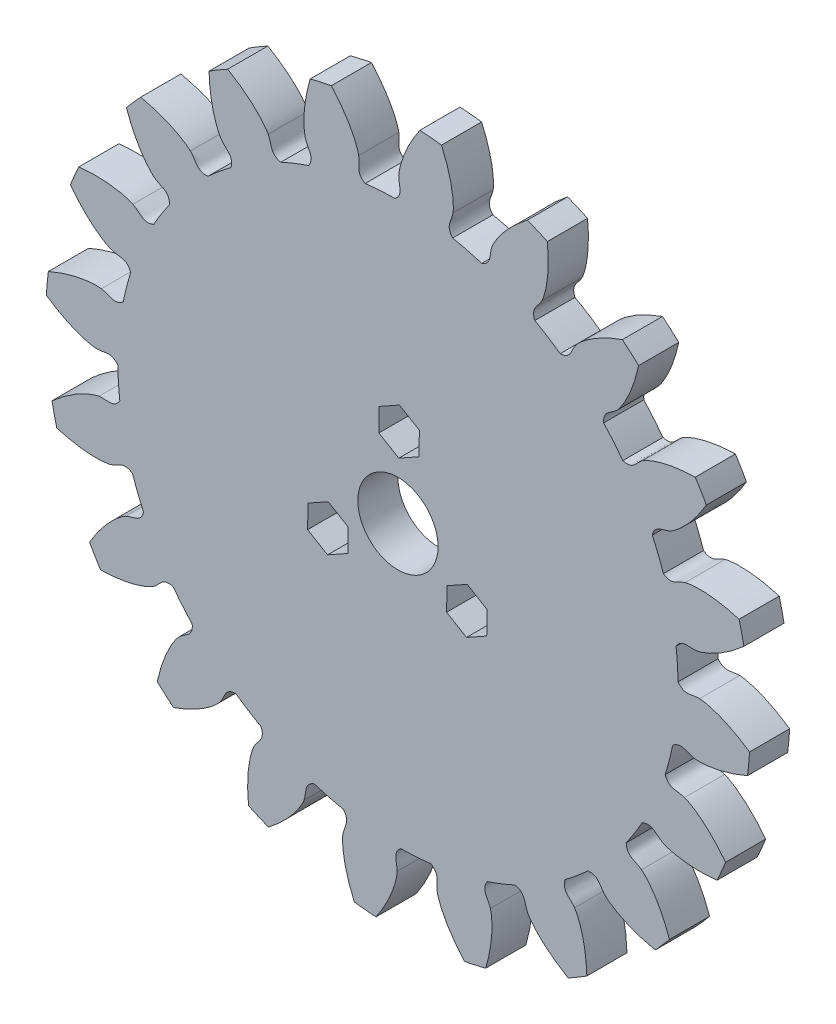
SolidWorks part; units mm, degrees
ref_plane "前视基准面" through (0, 0, 0) normal (0, 0, 1) x (1, 0, 0)
ref_plane "上视基准面" through (0, 0, 0) normal (0, 1, 0) x (1, 0, 0)
ref_plane "右视基准面" through (0, 0, 0) normal (1, 0, 0) x (0, 0, -1)
other "Configuration Table"
sketch "草图1" plane through (0, 0, 0) normal (0, 0, 1) x (1, 0, 0)
  line L0 (0, 0) -> (0.5841, 39.9957)
  line L1 (0, 0) -> (5.9496, 63.6903) construction
  line L2 (0, 0) -> (18.1411, 70.98) construction
  circle A0 centre (0, 0) radius 35
  circle A1 centre (0, 0) radius 44
  circle A2 centre (0, 0) radius 40
  spline S0 degree 4 poles (0, 37.5877) (0.0005, 37.6182) (0.0041, 37.7036) (0.0192, 37.8647) (0.0554, 38.1265) (0.1186, 38.4578) (0.2198, 38.8826) (0.4071, 39.5267) (0.6537, 40.2073) (0.9587, 40.9201) (1.2991, 41.6171) (1.5905, 42.1649) (1.9655, 42.8179) (2.4482, 43.5871) (3.054, 44.4613) (3.7979, 45.4264) (4.6021, 46.3721) (5.4478, 47.2803) (6.3318, 48.1521) (7.1346, 48.8825) (7.8437, 49.4869) (8.5651, 50.0721) (9.1825, 50.5475) (9.8023, 51.0032) (10.446, 51.4523) (10.9465, 51.791) (11.4923, 52.1442) (11.972, 52.447) (12.6893, 52.8789) (13.1234, 53.1293) (13.8248, 53.5233) (14.1422, 53.6882) (14.4284, 53.8421) (14.5134, 53.8845) (14.5753, 53.9169) (14.6088, 53.9346) knots 0 0 0 0 0 0.005377 0.015084 0.028532 0.04661 0.064855 0.092111 0.146842 0.174209 0.201575 0.228941 0.256307 0.307035 0.361767 0.4165 0.471232 0.525964 0.580697 0.635429 0.662795 0.690161 0.744894 0.77226 0.799626 0.826992 0.854358 0.881725 0.909091 0.954545 0.977273 0.988636 0.994318 1 1 1 1 1 construction
  spline S1 degree 4 poles (0, 37.5877) (0.0005, 37.6182) (0.0041, 37.7036) (0.0192, 37.8647) (0.0554, 38.1265) (0.1186, 38.4578) (0.2198, 38.8826) (0.4071, 39.5267) (0.6537, 40.2073) (0.9587, 40.9201) (1.2991, 41.6171) (1.5905, 42.1649) (1.9638, 42.8149) (2.2796, 43.3184) (2.5228, 43.6842) (2.684, 43.9181) knots 0 0 0 0 0 0.005377 0.015084 0.028532 0.04661 0.064855 0.092111 0.146842 0.174209 0.201575 0.228941 0.256307 0.306424 0.306424 0.306424 0.306424 0.306424
  spline S2 degree 3 poles (0, 37.5877) (-0.0182, 36.5489) (0.5928, 35.8025) (-0.3981, 34.9977) knots 0 0 0 0 1 1 1 1
  spline S3 degree 3 poles (6.9617, 36.9374) (6.7872, 35.9132) (6.0485, 35.2928) (6.8732, 34.3185) knots 0 0 0 0 1 1 1 1
  spline S4 degree 4 poles (6.9617, 36.9374) (6.9668, 36.9674) (6.9791, 37.052) (6.9942, 37.2131) (7.0071, 37.4771) (7.0063, 37.8143) (6.9855, 38.2505) (6.9207, 38.9182) (6.8045, 39.6327) (6.6368, 40.3897) (6.4314, 41.1376) (6.2464, 41.73) (6.0001, 42.4378) (5.783, 42.9912) (5.6117, 43.3956) (5.4966, 43.6553) knots 0 0 0 0 0 0.005377 0.015084 0.028532 0.04661 0.064855 0.092111 0.146842 0.174209 0.201575 0.228941 0.256307 0.306424 0.306424 0.306424 0.306424 0.306424
  spline S5 degree 3 poles (11.6152, 35.748) (11.2769, 34.7657) (11.6273, 33.867) (10.4363, 33.4079) knots 0 0 0 0 1 1 1 1
  spline S6 degree 4 poles (11.6152, 35.748) (11.6252, 35.7769) (11.655, 35.857) (11.7191, 36.0056) (11.8344, 36.2433) (11.9969, 36.5388) (12.2244, 36.9116) (12.6016, 37.4663) (13.0464, 38.0374) (13.5568, 38.621) (14.0959, 39.1787) (14.5424, 39.6097) (15.0982, 40.1125) (15.5541, 40.4939) (15.8985, 40.7665) (16.124, 40.9392) knots 0 0 0 0 0 0.005377 0.015084 0.028532 0.04661 0.064855 0.092111 0.146842 0.174209 0.201575 0.228941 0.256307 0.306424 0.306424 0.306424 0.306424 0.306424
  dimension "D1" = 88
  dimension "D2" = 70
  dimension "D3" = 80
  dimension "D4" = 4.5
  dimension "D5" = 9
sketch "草图2" plane through (0, 0, 0) normal (0, 0, 1) x (1, 0, 0)
  circle A0 centre (0, 0) radius 44 construction
  circle A1 centre (0, 0) radius 35 construction
  arc A2 (5.4966, 43.6553) -> (2.684, 43.9181) centre (0, 0) ccw
  arc A3 (10.4363, 33.4079) -> (6.8732, 34.3185) centre (0, 0) ccw
  arc A4 (18.7179, 39.8201) -> (16.124, 40.9392) centre (0, 0) ccw
  arc A5 (20.2491, 28.5478) -> (17.1418, 30.5149) centre (0, 0) ccw
  arc A6 (30.1068, 32.087) -> (27.9858, 33.9529) centre (0, 0) ccw
  arc A7 (28.0797, 20.8932) -> (25.7325, 23.7242) centre (0, 0) ccw
  arc A8 (38.5487, 21.2131) -> (37.1081, 23.643) centre (0, 0) ccw
  arc A9 (33.1618, 11.1935) -> (31.8042, 14.6113) centre (0, 0) ccw
  arc A10 (43.2172, 8.2626) -> (42.5979, 11.0188) centre (0, 0) ccw
  arc A11 (34.9977, 0.3981) -> (34.7628, 4.0681) centre (0, 0) ccw
  arc A12 (43.6553, -5.4966) -> (43.9181, -2.684) centre (0, 0) ccw
  arc A13 (33.4079, -10.4363) -> (34.3185, -6.8732) centre (0, 0) ccw
  arc A14 (39.8201, -18.7179) -> (40.9392, -16.124) centre (0, 0) ccw
  arc A15 (28.5478, -20.2491) -> (30.5149, -17.1418) centre (0, 0) ccw
  arc A16 (32.087, -30.1068) -> (33.9529, -27.9858) centre (0, 0) ccw
  arc A17 (20.8932, -28.0797) -> (23.7242, -25.7325) centre (0, 0) ccw
  arc A18 (21.2131, -38.5487) -> (23.643, -37.1081) centre (0, 0) ccw
  arc A19 (11.1935, -33.1618) -> (14.6113, -31.8042) centre (0, 0) ccw
  arc A20 (8.2626, -43.2172) -> (11.0188, -42.5979) centre (0, 0) ccw
  arc A21 (0.3981, -34.9977) -> (4.0681, -34.7628) centre (0, 0) ccw
  arc A22 (-5.4966, -43.6553) -> (-2.684, -43.9181) centre (0, 0) ccw
  arc A23 (-10.4363, -33.4079) -> (-6.8732, -34.3185) centre (0, 0) ccw
  arc A24 (-18.7179, -39.8201) -> (-16.124, -40.9392) centre (0, 0) ccw
  arc A25 (-20.2491, -28.5478) -> (-17.1418, -30.5149) centre (0, 0) ccw
  arc A26 (-30.1068, -32.087) -> (-27.9858, -33.9529) centre (0, 0) ccw
  arc A27 (-28.0797, -20.8932) -> (-25.7325, -23.7242) centre (0, 0) ccw
  arc A28 (-38.5487, -21.2131) -> (-37.1081, -23.643) centre (0, 0) ccw
  arc A29 (-33.1618, -11.1935) -> (-31.8042, -14.6113) centre (0, 0) ccw
  arc A30 (-43.2172, -8.2626) -> (-42.5979, -11.0188) centre (0, 0) ccw
  arc A31 (-34.9977, -0.3981) -> (-34.7628, -4.0681) centre (0, 0) ccw
  arc A32 (-43.6553, 5.4966) -> (-43.9181, 2.684) centre (0, 0) ccw
  arc A33 (-33.4079, 10.4363) -> (-34.3185, 6.8732) centre (0, 0) ccw
  arc A34 (-39.8201, 18.7179) -> (-40.9392, 16.124) centre (0, 0) ccw
  arc A35 (-28.5478, 20.2491) -> (-30.5149, 17.1418) centre (0, 0) ccw
  arc A36 (-32.087, 30.1068) -> (-33.9529, 27.9858) centre (0, 0) ccw
  arc A37 (-20.8932, 28.0797) -> (-23.7242, 25.7325) centre (0, 0) ccw
  arc A38 (-21.2131, 38.5487) -> (-23.643, 37.1081) centre (0, 0) ccw
  arc A39 (-11.1935, 33.1618) -> (-14.6113, 31.8042) centre (0, 0) ccw
  arc A40 (-8.2626, 43.2172) -> (-11.0188, 42.5979) centre (0, 0) ccw
  arc A41 (-0.3981, 34.9977) -> (-4.0681, 34.7628) centre (0, 0) ccw
  spline S1 degree 3 poles (-1849.2415, 781.0057) (1887.5351, -643.1311) (-1886.6119, 682.3975) (1900.1729, -609.9108) knots -9.305815 -9.305815 -9.305815 -9.305815 9.899878 9.899878 9.899878 9.899878 only from (6.9617, 36.9374) to (6.8732, 34.3185) construction
  spline S2 degree 4 poles (-1958.2337, 407.3557) (-32.4245, 37.9175) (5.4639, 33.0691) (6.895, 35.1809) (7.0071, 37.4771) (7.0063, 37.8143) (6.9855, 38.2505) (6.9207, 38.9182) (6.8045, 39.6327) (6.6368, 40.3897) (6.4314, 41.1376) (6.2464, 41.73) (-2.039, 65.5327) (-48.7915, 75.0281) (50.0761, 48.8312) (-1973.582, -244.5836) knots -0.3589 -0.3589 -0.3589 -0.3589 -0.3589 0.005377 0.015084 0.028532 0.04661 0.064855 0.092111 0.146842 0.174209 0.201575 0.228941 0.256307 4.620268 4.620268 4.620268 4.620268 4.620268 only from (6.9617, 36.9374) to (5.4966, 43.6553) construction
  spline S3 degree 3 poles (1961.8988, 424.9909) (-1973.9938, -282.4093) (1980.3591, 321.1673) (-1980.2601, -247.4231) knots -9.305815 -9.305815 -9.305815 -9.305815 9.899878 9.899878 9.899878 9.899878 only from (0, 37.5877) to (-0.3981, 34.9977) construction
  spline S4 degree 4 poles (1999.8006, 37.6189) (38.8863, 31.256) (0.7555, 33.509) (-0.2597, 35.8493) (0.0554, 38.1265) (0.1186, 38.4578) (0.2198, 38.8826) (0.4071, 39.5267) (0.6537, 40.2073) (0.9587, 40.9201) (1.2991, 41.6171) (1.5905, 42.1649) (14.1412, 64.0213) (61.8435, 64.6932) (-40.1656, 57.2611) (1894.1363, -605.8836) knots -0.3589 -0.3589 -0.3589 -0.3589 -0.3589 0.005377 0.015084 0.028532 0.04661 0.064855 0.092111 0.146842 0.174209 0.201575 0.228941 0.256307 4.620268 4.620268 4.620268 4.620268 4.620268 only from (0, 37.5877) to (2.684, 43.9181) construction
  spline S5 degree 3 poles (11.6152, 35.748) (11.2769, 34.7657) (11.6273, 33.867) (10.4363, 33.4079) knots 0 0 0 0 1 1 1 1
  spline S6 degree 3 poles (6.9617, 36.9374) (6.7872, 35.9132) (6.0485, 35.2928) (6.8732, 34.3185) knots 0 0 0 0 1 1 1 1
  spline S7 degree 4 poles (6.9617, 36.9374) (6.9668, 36.9674) (6.9791, 37.052) (6.9942, 37.2131) (7.0071, 37.4771) (7.0063, 37.8143) (6.9855, 38.2505) (6.9207, 38.9182) (6.8045, 39.6327) (6.6368, 40.3897) (6.4314, 41.1376) (6.2464, 41.73) (6.0001, 42.4378) (5.783, 42.9912) (5.6117, 43.3956) (5.4966, 43.6553) knots 0 0 0 0 0 0.005377 0.015084 0.028532 0.04661 0.064855 0.092111 0.146842 0.174209 0.201575 0.228941 0.256307 0.306424 0.306424 0.306424 0.306424 0.306424
  spline S8 degree 3 poles (0, 37.5877) (-0.0182, 36.5489) (0.5928, 35.8025) (-0.3981, 34.9977) knots 0 0 0 0 1 1 1 1
  spline S9 degree 4 poles (0, 37.5877) (0.0005, 37.6182) (0.0041, 37.7036) (0.0192, 37.8647) (0.0554, 38.1265) (0.1186, 38.4578) (0.2198, 38.8826) (0.4071, 39.5267) (0.6537, 40.2073) (0.9587, 40.9201) (1.2991, 41.6171) (1.5905, 42.1649) (1.9638, 42.8149) (2.2796, 43.3184) (2.5228, 43.6842) (2.684, 43.9181) knots 0 0 0 0 0 0.005377 0.015084 0.028532 0.04661 0.064855 0.092111 0.146842 0.174209 0.201575 0.228941 0.256307 0.306424 0.306424 0.306424 0.306424 0.306424
  spline S10 degree 4 poles (11.6152, 35.748) (11.6252, 35.7769) (11.655, 35.857) (11.7191, 36.0056) (11.8344, 36.2433) (11.9969, 36.5388) (12.2244, 36.9116) (12.6016, 37.4663) (13.0464, 38.0374) (13.5568, 38.621) (14.0959, 39.1787) (14.5424, 39.6097) (15.0982, 40.1125) (15.5541, 40.4939) (15.8985, 40.7665) (16.124, 40.9392) knots 0 0 0 0 0 0.005377 0.015084 0.028532 0.04661 0.064855 0.092111 0.146842 0.174209 0.201575 0.228941 0.256307 0.306424 0.306424 0.306424 0.306424 0.306424
  spline S11 degree 4 poles (18.0353, 32.9783) (18.0494, 33.0052) (18.0872, 33.0819) (18.1514, 33.2305) (18.2452, 33.4775) (18.3487, 33.7985) (18.4637, 34.2198) (18.6084, 34.8748) (18.7187, 35.5902) (18.793, 36.362) (18.8288, 37.1368) (18.836, 37.7573) (18.8204, 38.5066) (18.7849, 39.1) (18.747, 39.5376) (18.7179, 39.8201) knots 0 0 0 0 0 0.005377 0.015084 0.028532 0.04661 0.064855 0.092111 0.146842 0.174209 0.201575 0.228941 0.256307 0.306424 0.306424 0.306424 0.306424 0.306424
  spline S12 degree 3 poles (18.0353, 32.9783) (17.5528, 32.0581) (16.6586, 31.6964) (17.1418, 30.5149) knots 0 0 0 0 1 1 1 1
  spline S13 degree 3 poles (22.0935, 30.4091) (21.4682, 29.5794) (21.5237, 28.6164) (20.2491, 28.5478) knots 0 0 0 0 1 1 1 1
  spline S14 degree 4 poles (22.0935, 30.4091) (22.1118, 30.4334) (22.165, 30.5004) (22.2718, 30.6219) (22.455, 30.8124) (22.7008, 31.0433) (23.0324, 31.3274) (23.5626, 31.7385) (24.1621, 32.1442) (24.8278, 32.5415) (25.5129, 32.9053) (26.0707, 33.1772) (26.7547, 33.4837) (27.3061, 33.7055) (27.7179, 33.8584) (27.9858, 33.9529) knots 0 0 0 0 0 0.005377 0.015084 0.028532 0.04661 0.064855 0.092111 0.146842 0.174209 0.201575 0.228941 0.256307 0.306424 0.306424 0.306424 0.306424 0.306424
  spline S15 degree 4 poles (27.3434, 25.791) (27.3652, 25.8123) (27.4249, 25.8735) (27.5317, 25.995) (27.6973, 26.2009) (27.8949, 26.4742) (28.1345, 26.8393) (28.4746, 27.4176) (28.8005, 28.0639) (29.1097, 28.7749) (29.3832, 29.5008) (29.5817, 30.0887) (29.7985, 30.8062) (29.9481, 31.3814) (30.0473, 31.8093) (30.1068, 32.087) knots 0 0 0 0 0 0.005377 0.015084 0.028532 0.04661 0.064855 0.092111 0.146842 0.174209 0.201575 0.228941 0.256307 0.306424 0.306424 0.306424 0.306424 0.306424
  spline S16 degree 3 poles (27.3434, 25.791) (26.6002, 25.065) (25.638, 24.9972) (25.7325, 23.7242) knots 0 0 0 0 1 1 1 1
  spline S17 degree 3 poles (30.4091, 22.0935) (29.558, 21.4977) (29.3132, 20.5646) (28.0797, 20.8932) knots 0 0 0 0 1 1 1 1
  spline S18 degree 4 poles (30.4091, 22.0935) (30.4341, 22.111) (30.5053, 22.1583) (30.6445, 22.2408) (30.8775, 22.3654) (31.1827, 22.509) (31.5858, 22.6768) (32.2171, 22.9038) (32.9126, 23.1044) (33.6685, 23.2766) (34.4325, 23.4109) (35.047, 23.4971) (35.7922, 23.5772) (36.3852, 23.6177) (36.8241, 23.6359) (37.1081, 23.643) knots 0 0 0 0 0 0.005377 0.015084 0.028532 0.04661 0.064855 0.092111 0.146842 0.174209 0.201575 0.228941 0.256307 0.306424 0.306424 0.306424 0.306424 0.306424
  spline S19 degree 4 poles (33.975, 16.0791) (34.0023, 16.0926) (34.0779, 16.1324) (34.2171, 16.2149) (34.4382, 16.3596) (34.7106, 16.5585) (35.0513, 16.8317) (35.5534, 17.2766) (36.0631, 17.7905) (36.5769, 18.3712) (37.0613, 18.977) (37.4318, 19.4748) (37.8597, 20.0902) (38.1797, 20.591) (38.4063, 20.9673) (38.5487, 21.2131) knots 0 0 0 0 0 0.005377 0.015084 0.028532 0.04661 0.064855 0.092111 0.146842 0.174209 0.201575 0.228941 0.256307 0.306424 0.306424 0.306424 0.306424 0.306424
  spline S20 degree 3 poles (33.975, 16.0791) (33.0438, 15.6183) (32.1077, 15.8512) (31.8042, 14.6113) knots 0 0 0 0 1 1 1 1
  spline S21 degree 3 poles (35.748, 11.6152) (34.7545, 11.3116) (34.2333, 10.4998) (33.1618, 11.1935) knots 0 0 0 0 1 1 1 1
  spline S22 degree 4 poles (35.748, 11.6152) (35.7772, 11.6241) (35.8595, 11.6471) (36.0174, 11.6826) (36.2775, 11.729) (36.6121, 11.7713) (37.0474, 11.8063) (37.7179, 11.8272) (38.4414, 11.8031) (39.2135, 11.7332) (39.9816, 11.6249) (40.5927, 11.517) (41.3262, 11.3629) (41.9027, 11.2181) (42.3257, 11.0999) (42.5979, 11.0188) knots 0 0 0 0 0 0.005377 0.015084 0.028532 0.04661 0.064855 0.092111 0.146842 0.174209 0.201575 0.228941 0.256307 0.306424 0.306424 0.306424 0.306424 0.306424
  spline S23 degree 4 poles (37.2808, 4.7933) (37.311, 4.7977) (37.3952, 4.8122) (37.5531, 4.8476) (37.8081, 4.9169) (38.1286, 5.0219) (38.5371, 5.1764) (39.1521, 5.4444) (39.7957, 5.7757) (40.4637, 6.1691) (41.1116, 6.5957) (41.6178, 6.9545) (42.2149, 7.4076) (42.6741, 7.7851) (43.0058, 8.0729) (43.2172, 8.2626) knots 0 0 0 0 0 0.005377 0.015084 0.028532 0.04661 0.064855 0.092111 0.146842 0.174209 0.201575 0.228941 0.256307 0.306424 0.306424 0.306424 0.306424 0.306424
  spline S24 degree 3 poles (37.2808, 4.7933) (36.2529, 4.6428) (35.4346, 5.1536) (34.7628, 4.0681) knots 0 0 0 0 1 1 1 1
  spline S25 degree 3 poles (37.5877, 0) (36.5489, 0.0182) (35.8025, -0.5928) (34.9977, 0.3981) knots 0 0 0 0 1 1 1 1
  spline S26 degree 4 poles (37.5877, 0) (37.6182, -0.0005) (37.7036, -0.0041) (37.8647, -0.0192) (38.1265, -0.0554) (38.4578, -0.1186) (38.8826, -0.2198) (39.5267, -0.4071) (40.2073, -0.6537) (40.9201, -0.9587) (41.6171, -1.2991) (42.1649, -1.5905) (42.8149, -1.9638) (43.3184, -2.2796) (43.6842, -2.5228) (43.9181, -2.684) knots 0 0 0 0 0 0.005377 0.015084 0.028532 0.04661 0.064855 0.092111 0.146842 0.174209 0.201575 0.228941 0.256307 0.306424 0.306424 0.306424 0.306424 0.306424
  spline S27 degree 4 poles (36.9374, -6.9617) (36.9674, -6.9668) (37.052, -6.9791) (37.2131, -6.9942) (37.4771, -7.0071) (37.8143, -7.0063) (38.2505, -6.9855) (38.9182, -6.9207) (39.6327, -6.8045) (40.3897, -6.6368) (41.1376, -6.4314) (41.73, -6.2464) (42.4378, -6.0001) (42.9912, -5.783) (43.3956, -5.6117) (43.6553, -5.4966) knots 0 0 0 0 0 0.005377 0.015084 0.028532 0.04661 0.064855 0.092111 0.146842 0.174209 0.201575 0.228941 0.256307 0.306424 0.306424 0.306424 0.306424 0.306424
  spline S28 degree 3 poles (36.9374, -6.9617) (35.9132, -6.7872) (35.2928, -6.0485) (34.3185, -6.8732) knots 0 0 0 0 1 1 1 1
  spline S29 degree 3 poles (35.748, -11.6152) (34.7657, -11.2769) (33.867, -11.6273) (33.4079, -10.4363) knots 0 0 0 0 1 1 1 1
  spline S30 degree 4 poles (35.748, -11.6152) (35.7769, -11.6252) (35.857, -11.655) (36.0056, -11.7191) (36.2433, -11.8344) (36.5388, -11.9969) (36.9116, -12.2244) (37.4663, -12.6016) (38.0374, -13.0464) (38.621, -13.5568) (39.1787, -14.0959) (39.6097, -14.5424) (40.1125, -15.0982) (40.4939, -15.5541) (40.7665, -15.8985) (40.9392, -16.124) knots 0 0 0 0 0 0.005377 0.015084 0.028532 0.04661 0.064855 0.092111 0.146842 0.174209 0.201575 0.228941 0.256307 0.306424 0.306424 0.306424 0.306424 0.306424
  spline S31 degree 4 poles (32.9783, -18.0353) (33.0052, -18.0494) (33.0819, -18.0872) (33.2305, -18.1514) (33.4775, -18.2452) (33.7985, -18.3487) (34.2198, -18.4637) (34.8748, -18.6084) (35.5902, -18.7187) (36.362, -18.793) (37.1368, -18.8288) (37.7573, -18.836) (38.5066, -18.8204) (39.1, -18.7849) (39.5376, -18.747) (39.8201, -18.7179) knots 0 0 0 0 0 0.005377 0.015084 0.028532 0.04661 0.064855 0.092111 0.146842 0.174209 0.201575 0.228941 0.256307 0.306424 0.306424 0.306424 0.306424 0.306424
  spline S32 degree 3 poles (32.9783, -18.0353) (32.0581, -17.5528) (31.6964, -16.6586) (30.5149, -17.1418) knots 0 0 0 0 1 1 1 1
  spline S33 degree 3 poles (30.4091, -22.0935) (29.5794, -21.4682) (28.6164, -21.5237) (28.5478, -20.2491) knots 0 0 0 0 1 1 1 1
  spline S34 degree 4 poles (30.4091, -22.0935) (30.4334, -22.1118) (30.5004, -22.165) (30.6219, -22.2718) (30.8124, -22.455) (31.0433, -22.7008) (31.3274, -23.0324) (31.7385, -23.5626) (32.1442, -24.1621) (32.5415, -24.8278) (32.9053, -25.5129) (33.1772, -26.0707) (33.4837, -26.7547) (33.7055, -27.3061) (33.8584, -27.7179) (33.9529, -27.9858) knots 0 0 0 0 0 0.005377 0.015084 0.028532 0.04661 0.064855 0.092111 0.146842 0.174209 0.201575 0.228941 0.256307 0.306424 0.306424 0.306424 0.306424 0.306424
  spline S35 degree 4 poles (25.791, -27.3434) (25.8123, -27.3652) (25.8735, -27.4249) (25.995, -27.5317) (26.2009, -27.6973) (26.4742, -27.8949) (26.8393, -28.1345) (27.4176, -28.4746) (28.0639, -28.8005) (28.7749, -29.1097) (29.5008, -29.3832) (30.0887, -29.5817) (30.8062, -29.7985) (31.3814, -29.9481) (31.8093, -30.0473) (32.087, -30.1068) knots 0 0 0 0 0 0.005377 0.015084 0.028532 0.04661 0.064855 0.092111 0.146842 0.174209 0.201575 0.228941 0.256307 0.306424 0.306424 0.306424 0.306424 0.306424
  spline S36 degree 3 poles (25.791, -27.3434) (25.065, -26.6002) (24.9972, -25.638) (23.7242, -25.7325) knots 0 0 0 0 1 1 1 1
  spline S37 degree 3 poles (22.0935, -30.4091) (21.4977, -29.558) (20.5646, -29.3132) (20.8932, -28.0797) knots 0 0 0 0 1 1 1 1
  spline S38 degree 4 poles (22.0935, -30.4091) (22.111, -30.4341) (22.1583, -30.5053) (22.2408, -30.6445) (22.3654, -30.8775) (22.509, -31.1827) (22.6768, -31.5858) (22.9038, -32.2171) (23.1044, -32.9126) (23.2766, -33.6685) (23.4109, -34.4325) (23.4971, -35.047) (23.5772, -35.7922) (23.6177, -36.3852) (23.6359, -36.8241) (23.643, -37.1081) knots 0 0 0 0 0 0.005377 0.015084 0.028532 0.04661 0.064855 0.092111 0.146842 0.174209 0.201575 0.228941 0.256307 0.306424 0.306424 0.306424 0.306424 0.306424
  spline S39 degree 4 poles (16.0791, -33.975) (16.0926, -34.0023) (16.1324, -34.0779) (16.2149, -34.2171) (16.3596, -34.4382) (16.5585, -34.7106) (16.8317, -35.0513) (17.2766, -35.5534) (17.7905, -36.0631) (18.3712, -36.5769) (18.977, -37.0613) (19.4748, -37.4318) (20.0902, -37.8597) (20.591, -38.1797) (20.9673, -38.4063) (21.2131, -38.5487) knots 0 0 0 0 0 0.005377 0.015084 0.028532 0.04661 0.064855 0.092111 0.146842 0.174209 0.201575 0.228941 0.256307 0.306424 0.306424 0.306424 0.306424 0.306424
  spline S40 degree 3 poles (16.0791, -33.975) (15.6183, -33.0438) (15.8512, -32.1077) (14.6113, -31.8042) knots 0 0 0 0 1 1 1 1
  spline S41 degree 3 poles (11.6152, -35.748) (11.3116, -34.7545) (10.4998, -34.2333) (11.1935, -33.1618) knots 0 0 0 0 1 1 1 1
  spline S42 degree 4 poles (11.6152, -35.748) (11.6241, -35.7772) (11.6471, -35.8595) (11.6826, -36.0174) (11.729, -36.2775) (11.7713, -36.6121) (11.8063, -37.0474) (11.8272, -37.7179) (11.8031, -38.4414) (11.7332, -39.2135) (11.6249, -39.9816) (11.517, -40.5927) (11.3629, -41.3262) (11.2181, -41.9027) (11.0999, -42.3257) (11.0188, -42.5979) knots 0 0 0 0 0 0.005377 0.015084 0.028532 0.04661 0.064855 0.092111 0.146842 0.174209 0.201575 0.228941 0.256307 0.306424 0.306424 0.306424 0.306424 0.306424
  spline S43 degree 4 poles (4.7933, -37.2808) (4.7977, -37.311) (4.8122, -37.3952) (4.8476, -37.5531) (4.9169, -37.8081) (5.0219, -38.1286) (5.1764, -38.5371) (5.4444, -39.1521) (5.7757, -39.7957) (6.1691, -40.4637) (6.5957, -41.1116) (6.9545, -41.6178) (7.4076, -42.2149) (7.7851, -42.6741) (8.0729, -43.0058) (8.2626, -43.2172) knots 0 0 0 0 0 0.005377 0.015084 0.028532 0.04661 0.064855 0.092111 0.146842 0.174209 0.201575 0.228941 0.256307 0.306424 0.306424 0.306424 0.306424 0.306424
  spline S44 degree 3 poles (4.7933, -37.2808) (4.6428, -36.2529) (5.1536, -35.4346) (4.0681, -34.7628) knots 0 0 0 0 1 1 1 1
  spline S45 degree 3 poles (0, -37.5877) (0.0182, -36.5489) (-0.5928, -35.8025) (0.3981, -34.9977) knots 0 0 0 0 1 1 1 1
  spline S46 degree 4 poles (0, -37.5877) (-0.0005, -37.6182) (-0.0041, -37.7036) (-0.0192, -37.8647) (-0.0554, -38.1265) (-0.1186, -38.4578) (-0.2198, -38.8826) (-0.4071, -39.5267) (-0.6537, -40.2073) (-0.9587, -40.9201) (-1.2991, -41.6171) (-1.5905, -42.1649) (-1.9638, -42.8149) (-2.2796, -43.3184) (-2.5228, -43.6842) (-2.684, -43.9181) knots 0 0 0 0 0 0.005377 0.015084 0.028532 0.04661 0.064855 0.092111 0.146842 0.174209 0.201575 0.228941 0.256307 0.306424 0.306424 0.306424 0.306424 0.306424
  spline S47 degree 4 poles (-6.9617, -36.9374) (-6.9668, -36.9674) (-6.9791, -37.052) (-6.9942, -37.2131) (-7.0071, -37.4771) (-7.0063, -37.8143) (-6.9855, -38.2505) (-6.9207, -38.9182) (-6.8045, -39.6327) (-6.6368, -40.3897) (-6.4314, -41.1376) (-6.2464, -41.73) (-6.0001, -42.4378) (-5.783, -42.9912) (-5.6117, -43.3956) (-5.4966, -43.6553) knots 0 0 0 0 0 0.005377 0.015084 0.028532 0.04661 0.064855 0.092111 0.146842 0.174209 0.201575 0.228941 0.256307 0.306424 0.306424 0.306424 0.306424 0.306424
  spline S48 degree 3 poles (-6.9617, -36.9374) (-6.7872, -35.9132) (-6.0485, -35.2928) (-6.8732, -34.3185) knots 0 0 0 0 1 1 1 1
  spline S49 degree 3 poles (-11.6152, -35.748) (-11.2769, -34.7657) (-11.6273, -33.867) (-10.4363, -33.4079) knots 0 0 0 0 1 1 1 1
  spline S50 degree 4 poles (-11.6152, -35.748) (-11.6252, -35.7769) (-11.655, -35.857) (-11.7191, -36.0056) (-11.8344, -36.2433) (-11.9969, -36.5388) (-12.2244, -36.9116) (-12.6016, -37.4663) (-13.0464, -38.0374) (-13.5568, -38.621) (-14.0959, -39.1787) (-14.5424, -39.6097) (-15.0982, -40.1125) (-15.5541, -40.4939) (-15.8985, -40.7665) (-16.124, -40.9392) knots 0 0 0 0 0 0.005377 0.015084 0.028532 0.04661 0.064855 0.092111 0.146842 0.174209 0.201575 0.228941 0.256307 0.306424 0.306424 0.306424 0.306424 0.306424
  spline S51 degree 4 poles (-18.0353, -32.9783) (-18.0494, -33.0052) (-18.0872, -33.0819) (-18.1514, -33.2305) (-18.2452, -33.4775) (-18.3487, -33.7985) (-18.4637, -34.2198) (-18.6084, -34.8748) (-18.7187, -35.5902) (-18.793, -36.362) (-18.8288, -37.1368) (-18.836, -37.7573) (-18.8204, -38.5066) (-18.7849, -39.1) (-18.747, -39.5376) (-18.7179, -39.8201) knots 0 0 0 0 0 0.005377 0.015084 0.028532 0.04661 0.064855 0.092111 0.146842 0.174209 0.201575 0.228941 0.256307 0.306424 0.306424 0.306424 0.306424 0.306424
  spline S52 degree 3 poles (-18.0353, -32.9783) (-17.5528, -32.0581) (-16.6586, -31.6964) (-17.1418, -30.5149) knots 0 0 0 0 1 1 1 1
  spline S53 degree 3 poles (-22.0935, -30.4091) (-21.4682, -29.5794) (-21.5237, -28.6164) (-20.2491, -28.5478) knots 0 0 0 0 1 1 1 1
  spline S54 degree 4 poles (-22.0935, -30.4091) (-22.1118, -30.4334) (-22.165, -30.5004) (-22.2718, -30.6219) (-22.455, -30.8124) (-22.7008, -31.0433) (-23.0324, -31.3274) (-23.5626, -31.7385) (-24.1621, -32.1442) (-24.8278, -32.5415) (-25.5129, -32.9053) (-26.0707, -33.1772) (-26.7547, -33.4837) (-27.3061, -33.7055) (-27.7179, -33.8584) (-27.9858, -33.9529) knots 0 0 0 0 0 0.005377 0.015084 0.028532 0.04661 0.064855 0.092111 0.146842 0.174209 0.201575 0.228941 0.256307 0.306424 0.306424 0.306424 0.306424 0.306424
  spline S55 degree 4 poles (-27.3434, -25.791) (-27.3652, -25.8123) (-27.4249, -25.8735) (-27.5317, -25.995) (-27.6973, -26.2009) (-27.8949, -26.4742) (-28.1345, -26.8393) (-28.4746, -27.4176) (-28.8005, -28.0639) (-29.1097, -28.7749) (-29.3832, -29.5008) (-29.5817, -30.0887) (-29.7985, -30.8062) (-29.9481, -31.3814) (-30.0473, -31.8093) (-30.1068, -32.087) knots 0 0 0 0 0 0.005377 0.015084 0.028532 0.04661 0.064855 0.092111 0.146842 0.174209 0.201575 0.228941 0.256307 0.306424 0.306424 0.306424 0.306424 0.306424
  spline S56 degree 3 poles (-27.3434, -25.791) (-26.6002, -25.065) (-25.638, -24.9972) (-25.7325, -23.7242) knots 0 0 0 0 1 1 1 1
  spline S57 degree 3 poles (-30.4091, -22.0935) (-29.558, -21.4977) (-29.3132, -20.5646) (-28.0797, -20.8932) knots 0 0 0 0 1 1 1 1
  spline S58 degree 4 poles (-30.4091, -22.0935) (-30.4341, -22.111) (-30.5053, -22.1583) (-30.6445, -22.2408) (-30.8775, -22.3654) (-31.1827, -22.509) (-31.5858, -22.6768) (-32.2171, -22.9038) (-32.9126, -23.1044) (-33.6685, -23.2766) (-34.4325, -23.4109) (-35.047, -23.4971) (-35.7922, -23.5772) (-36.3852, -23.6177) (-36.8241, -23.6359) (-37.1081, -23.643) knots 0 0 0 0 0 0.005377 0.015084 0.028532 0.04661 0.064855 0.092111 0.146842 0.174209 0.201575 0.228941 0.256307 0.306424 0.306424 0.306424 0.306424 0.306424
  spline S59 degree 4 poles (-33.975, -16.0791) (-34.0023, -16.0926) (-34.0779, -16.1324) (-34.2171, -16.2149) (-34.4382, -16.3596) (-34.7106, -16.5585) (-35.0513, -16.8317) (-35.5534, -17.2766) (-36.0631, -17.7905) (-36.5769, -18.3712) (-37.0613, -18.977) (-37.4318, -19.4748) (-37.8597, -20.0902) (-38.1797, -20.591) (-38.4063, -20.9673) (-38.5487, -21.2131) knots 0 0 0 0 0 0.005377 0.015084 0.028532 0.04661 0.064855 0.092111 0.146842 0.174209 0.201575 0.228941 0.256307 0.306424 0.306424 0.306424 0.306424 0.306424
  spline S60 degree 3 poles (-33.975, -16.0791) (-33.0438, -15.6183) (-32.1077, -15.8512) (-31.8042, -14.6113) knots 0 0 0 0 1 1 1 1
  spline S61 degree 3 poles (-35.748, -11.6152) (-34.7545, -11.3116) (-34.2333, -10.4998) (-33.1618, -11.1935) knots 0 0 0 0 1 1 1 1
  spline S62 degree 4 poles (-35.748, -11.6152) (-35.7772, -11.6241) (-35.8595, -11.6471) (-36.0174, -11.6826) (-36.2775, -11.729) (-36.6121, -11.7713) (-37.0474, -11.8063) (-37.7179, -11.8272) (-38.4414, -11.8031) (-39.2135, -11.7332) (-39.9816, -11.6249) (-40.5927, -11.517) (-41.3262, -11.3629) (-41.9027, -11.2181) (-42.3257, -11.0999) (-42.5979, -11.0188) knots 0 0 0 0 0 0.005377 0.015084 0.028532 0.04661 0.064855 0.092111 0.146842 0.174209 0.201575 0.228941 0.256307 0.306424 0.306424 0.306424 0.306424 0.306424
  spline S63 degree 4 poles (-37.2808, -4.7933) (-37.311, -4.7977) (-37.3952, -4.8122) (-37.5531, -4.8476) (-37.8081, -4.9169) (-38.1286, -5.0219) (-38.5371, -5.1764) (-39.1521, -5.4444) (-39.7957, -5.7757) (-40.4637, -6.1691) (-41.1116, -6.5957) (-41.6178, -6.9545) (-42.2149, -7.4076) (-42.6741, -7.7851) (-43.0058, -8.0729) (-43.2172, -8.2626) knots 0 0 0 0 0 0.005377 0.015084 0.028532 0.04661 0.064855 0.092111 0.146842 0.174209 0.201575 0.228941 0.256307 0.306424 0.306424 0.306424 0.306424 0.306424
  spline S64 degree 3 poles (-37.2808, -4.7933) (-36.2529, -4.6428) (-35.4346, -5.1536) (-34.7628, -4.0681) knots 0 0 0 0 1 1 1 1
  spline S65 degree 3 poles (-37.5877, 0) (-36.5489, -0.0182) (-35.8025, 0.5928) (-34.9977, -0.3981) knots 0 0 0 0 1 1 1 1
  spline S66 degree 4 poles (-37.5877, 0) (-37.6182, 0.0005) (-37.7036, 0.0041) (-37.8647, 0.0192) (-38.1265, 0.0554) (-38.4578, 0.1186) (-38.8826, 0.2198) (-39.5267, 0.4071) (-40.2073, 0.6537) (-40.9201, 0.9587) (-41.6171, 1.2991) (-42.1649, 1.5905) (-42.8149, 1.9638) (-43.3184, 2.2796) (-43.6842, 2.5228) (-43.9181, 2.684) knots 0 0 0 0 0 0.005377 0.015084 0.028532 0.04661 0.064855 0.092111 0.146842 0.174209 0.201575 0.228941 0.256307 0.306424 0.306424 0.306424 0.306424 0.306424
  spline S67 degree 4 poles (-36.9374, 6.9617) (-36.9674, 6.9668) (-37.052, 6.9791) (-37.2131, 6.9942) (-37.4771, 7.0071) (-37.8143, 7.0063) (-38.2505, 6.9855) (-38.9182, 6.9207) (-39.6327, 6.8045) (-40.3897, 6.6368) (-41.1376, 6.4314) (-41.73, 6.2464) (-42.4378, 6.0001) (-42.9912, 5.783) (-43.3956, 5.6117) (-43.6553, 5.4966) knots 0 0 0 0 0 0.005377 0.015084 0.028532 0.04661 0.064855 0.092111 0.146842 0.174209 0.201575 0.228941 0.256307 0.306424 0.306424 0.306424 0.306424 0.306424
  spline S68 degree 3 poles (-36.9374, 6.9617) (-35.9132, 6.7872) (-35.2928, 6.0485) (-34.3185, 6.8732) knots 0 0 0 0 1 1 1 1
  spline S69 degree 3 poles (-35.748, 11.6152) (-34.7657, 11.2769) (-33.867, 11.6273) (-33.4079, 10.4363) knots 0 0 0 0 1 1 1 1
  spline S70 degree 4 poles (-35.748, 11.6152) (-35.7769, 11.6252) (-35.857, 11.655) (-36.0056, 11.7191) (-36.2433, 11.8344) (-36.5388, 11.9969) (-36.9116, 12.2244) (-37.4663, 12.6016) (-38.0374, 13.0464) (-38.621, 13.5568) (-39.1787, 14.0959) (-39.6097, 14.5424) (-40.1125, 15.0982) (-40.4939, 15.5541) (-40.7665, 15.8985) (-40.9392, 16.124) knots 0 0 0 0 0 0.005377 0.015084 0.028532 0.04661 0.064855 0.092111 0.146842 0.174209 0.201575 0.228941 0.256307 0.306424 0.306424 0.306424 0.306424 0.306424
  spline S71 degree 4 poles (-32.9783, 18.0353) (-33.0052, 18.0494) (-33.0819, 18.0872) (-33.2305, 18.1514) (-33.4775, 18.2452) (-33.7985, 18.3487) (-34.2198, 18.4637) (-34.8748, 18.6084) (-35.5902, 18.7187) (-36.362, 18.793) (-37.1368, 18.8288) (-37.7573, 18.836) (-38.5066, 18.8204) (-39.1, 18.7849) (-39.5376, 18.747) (-39.8201, 18.7179) knots 0 0 0 0 0 0.005377 0.015084 0.028532 0.04661 0.064855 0.092111 0.146842 0.174209 0.201575 0.228941 0.256307 0.306424 0.306424 0.306424 0.306424 0.306424
  spline S72 degree 3 poles (-32.9783, 18.0353) (-32.0581, 17.5528) (-31.6964, 16.6586) (-30.5149, 17.1418) knots 0 0 0 0 1 1 1 1
  spline S73 degree 3 poles (-30.4091, 22.0935) (-29.5794, 21.4682) (-28.6164, 21.5237) (-28.5478, 20.2491) knots 0 0 0 0 1 1 1 1
  spline S74 degree 4 poles (-30.4091, 22.0935) (-30.4334, 22.1118) (-30.5004, 22.165) (-30.6219, 22.2718) (-30.8124, 22.455) (-31.0433, 22.7008) (-31.3274, 23.0324) (-31.7385, 23.5626) (-32.1442, 24.1621) (-32.5415, 24.8278) (-32.9053, 25.5129) (-33.1772, 26.0707) (-33.4837, 26.7547) (-33.7055, 27.3061) (-33.8584, 27.7179) (-33.9529, 27.9858) knots 0 0 0 0 0 0.005377 0.015084 0.028532 0.04661 0.064855 0.092111 0.146842 0.174209 0.201575 0.228941 0.256307 0.306424 0.306424 0.306424 0.306424 0.306424
  spline S75 degree 4 poles (-25.791, 27.3434) (-25.8123, 27.3652) (-25.8735, 27.4249) (-25.995, 27.5317) (-26.2009, 27.6973) (-26.4742, 27.8949) (-26.8393, 28.1345) (-27.4176, 28.4746) (-28.0639, 28.8005) (-28.7749, 29.1097) (-29.5008, 29.3832) (-30.0887, 29.5817) (-30.8062, 29.7985) (-31.3814, 29.9481) (-31.8093, 30.0473) (-32.087, 30.1068) knots 0 0 0 0 0 0.005377 0.015084 0.028532 0.04661 0.064855 0.092111 0.146842 0.174209 0.201575 0.228941 0.256307 0.306424 0.306424 0.306424 0.306424 0.306424
  spline S76 degree 3 poles (-25.791, 27.3434) (-25.065, 26.6002) (-24.9972, 25.638) (-23.7242, 25.7325) knots 0 0 0 0 1 1 1 1
  spline S77 degree 3 poles (-22.0935, 30.4091) (-21.4977, 29.558) (-20.5646, 29.3132) (-20.8932, 28.0797) knots 0 0 0 0 1 1 1 1
  spline S78 degree 4 poles (-22.0935, 30.4091) (-22.111, 30.4341) (-22.1583, 30.5053) (-22.2408, 30.6445) (-22.3654, 30.8775) (-22.509, 31.1827) (-22.6768, 31.5858) (-22.9038, 32.2171) (-23.1044, 32.9126) (-23.2766, 33.6685) (-23.4109, 34.4325) (-23.4971, 35.047) (-23.5772, 35.7922) (-23.6177, 36.3852) (-23.6359, 36.8241) (-23.643, 37.1081) knots 0 0 0 0 0 0.005377 0.015084 0.028532 0.04661 0.064855 0.092111 0.146842 0.174209 0.201575 0.228941 0.256307 0.306424 0.306424 0.306424 0.306424 0.306424
  spline S79 degree 4 poles (-16.0791, 33.975) (-16.0926, 34.0023) (-16.1324, 34.0779) (-16.2149, 34.2171) (-16.3596, 34.4382) (-16.5585, 34.7106) (-16.8317, 35.0513) (-17.2766, 35.5534) (-17.7905, 36.0631) (-18.3712, 36.5769) (-18.977, 37.0613) (-19.4748, 37.4318) (-20.0902, 37.8597) (-20.591, 38.1797) (-20.9673, 38.4063) (-21.2131, 38.5487) knots 0 0 0 0 0 0.005377 0.015084 0.028532 0.04661 0.064855 0.092111 0.146842 0.174209 0.201575 0.228941 0.256307 0.306424 0.306424 0.306424 0.306424 0.306424
  spline S80 degree 3 poles (-16.0791, 33.975) (-15.6183, 33.0438) (-15.8512, 32.1077) (-14.6113, 31.8042) knots 0 0 0 0 1 1 1 1
  spline S81 degree 3 poles (-11.6152, 35.748) (-11.3116, 34.7545) (-10.4998, 34.2333) (-11.1935, 33.1618) knots 0 0 0 0 1 1 1 1
  spline S82 degree 4 poles (-11.6152, 35.748) (-11.6241, 35.7772) (-11.6471, 35.8595) (-11.6826, 36.0174) (-11.729, 36.2775) (-11.7713, 36.6121) (-11.8063, 37.0474) (-11.8272, 37.7179) (-11.8031, 38.4414) (-11.7332, 39.2135) (-11.6249, 39.9816) (-11.517, 40.5927) (-11.3629, 41.3262) (-11.2181, 41.9027) (-11.0999, 42.3257) (-11.0188, 42.5979) knots 0 0 0 0 0 0.005377 0.015084 0.028532 0.04661 0.064855 0.092111 0.146842 0.174209 0.201575 0.228941 0.256307 0.306424 0.306424 0.306424 0.306424 0.306424
  spline S83 degree 4 poles (-4.7933, 37.2808) (-4.7977, 37.311) (-4.8122, 37.3952) (-4.8476, 37.5531) (-4.9169, 37.8081) (-5.0219, 38.1286) (-5.1764, 38.5371) (-5.4444, 39.1521) (-5.7757, 39.7957) (-6.1691, 40.4637) (-6.5957, 41.1116) (-6.9545, 41.6178) (-7.4076, 42.2149) (-7.7851, 42.6741) (-8.0729, 43.0058) (-8.2626, 43.2172) knots 0 0 0 0 0 0.005377 0.015084 0.028532 0.04661 0.064855 0.092111 0.146842 0.174209 0.201575 0.228941 0.256307 0.306424 0.306424 0.306424 0.306424 0.306424
  spline S84 degree 3 poles (-4.7933, 37.2808) (-4.6428, 36.2529) (-5.1536, 35.4346) (-4.0681, 34.7628) knots 0 0 0 0 1 1 1 1
  point P8 (6.5065, 35.4332)
  point P149 (0, 0)
  dimension "D1" = 20
sketch "草图3" plane through (0, 0, 0) normal (0, 0, 1) x (1, 0, 0)
  arc A1065 (-21.2144, 38.4338) -> (-23.5416, 37.0541) centre (0, 0) ccw
  arc A1066 (-20.8056, 28.0203) -> (-23.6821, 25.6353) centre (0, 0) ccw
  arc A1067 (-32.0528, 29.9971) -> (-33.8397, 27.9658) centre (0, 0) ccw
  arc A1068 (-28.446, 20.2196) -> (-30.4447, 17.0625) centre (0, 0) ccw
  arc A1069 (-39.7536, 18.6241) -> (-40.8254, 16.14) centre (0, 0) ccw
  arc A1070 (-33.302, 10.4397) -> (-34.2273, 6.8195) centre (0, 0) ccw
  arc A1071 (-43.5631, 5.428) -> (-43.8148, 2.7343) centre (0, 0) ccw
  arc A1072 (-34.8981, -0.3622) -> (-34.6594, -4.0911) centre (0, 0) ccw
  arc A1073 (-43.1084, -8.2994) -> (-42.5153, -10.939) centre (0, 0) ccw
  arc A1074 (-33.0782, -11.1285) -> (-31.6988, -14.6012) centre (0, 0) ccw
  arc A1075 (-38.4338, -21.2144) -> (-37.0541, -23.5416) centre (0, 0) ccw
  arc A1076 (-28.0203, -20.8056) -> (-25.6353, -23.6821) centre (0, 0) ccw
  arc A1077 (-29.9971, -32.0528) -> (-27.9658, -33.8397) centre (0, 0) ccw
  arc A1078 (-20.2196, -28.446) -> (-17.0625, -30.4447) centre (0, 0) ccw
  arc A1079 (-18.6241, -39.7536) -> (-16.14, -40.8254) centre (0, 0) ccw
  arc A1080 (-10.4397, -33.302) -> (-6.8195, -34.2273) centre (0, 0) ccw
  arc A1081 (-5.428, -43.5631) -> (-2.7343, -43.8148) centre (0, 0) ccw
  arc A1082 (0.3622, -34.8981) -> (4.0911, -34.6594) centre (0, 0) ccw
  arc A1083 (8.2994, -43.1084) -> (10.939, -42.5153) centre (0, 0) ccw
  arc A1084 (11.1285, -33.0782) -> (14.6012, -31.6988) centre (0, 0) ccw
  arc A1085 (21.2144, -38.4338) -> (23.5416, -37.0541) centre (0, 0) ccw
  arc A1086 (20.8056, -28.0203) -> (23.6821, -25.6353) centre (0, 0) ccw
  arc A1087 (32.0528, -29.9971) -> (33.8397, -27.9658) centre (0, 0) ccw
  arc A1088 (28.446, -20.2196) -> (30.4447, -17.0625) centre (0, 0) ccw
  arc A1089 (39.7536, -18.6241) -> (40.8254, -16.14) centre (0, 0) ccw
  arc A1090 (33.302, -10.4397) -> (34.2273, -6.8195) centre (0, 0) ccw
  arc A1091 (43.5631, -5.428) -> (43.8148, -2.7343) centre (0, 0) ccw
  arc A1092 (34.8981, 0.3622) -> (34.6594, 4.0911) centre (0, 0) ccw
  arc A1093 (43.1084, 8.2994) -> (42.5153, 10.939) centre (0, 0) ccw
  arc A1094 (33.0782, 11.1285) -> (31.6988, 14.6012) centre (0, 0) ccw
  arc A1095 (38.4338, 21.2144) -> (37.0541, 23.5416) centre (0, 0) ccw
  arc A1096 (28.0203, 20.8056) -> (25.6353, 23.6821) centre (0, 0) ccw
  arc A1097 (29.9971, 32.0528) -> (27.9658, 33.8397) centre (0, 0) ccw
  arc A1098 (20.2196, 28.446) -> (17.0625, 30.4447) centre (0, 0) ccw
  arc A1099 (18.6241, 39.7536) -> (16.14, 40.8254) centre (0, 0) ccw
  arc A1100 (10.4397, 33.302) -> (6.8195, 34.2273) centre (0, 0) ccw
  arc A1101 (5.428, 43.5631) -> (2.7343, 43.8148) centre (0, 0) ccw
  arc A1102 (-0.3622, 34.8981) -> (-4.0911, 34.6594) centre (0, 0) ccw
  arc A1103 (-8.2994, 43.1084) -> (-10.939, 42.5153) centre (0, 0) ccw
  arc A1104 (-11.1285, 33.0782) -> (-14.6012, 31.6988) centre (0, 0) ccw
  arc A1105 (-21.2144, 38.4338) -> (-23.5416, 37.0541) centre (0, 0) ccw
  arc A1106 (-20.8056, 28.0203) -> (-23.6821, 25.6353) centre (0, 0) ccw
  arc A1107 (-32.0528, 29.9971) -> (-33.8397, 27.9658) centre (0, 0) ccw
  arc A1108 (-28.446, 20.2196) -> (-30.4447, 17.0625) centre (0, 0) ccw
  arc A1109 (-39.7536, 18.6241) -> (-40.8254, 16.14) centre (0, 0) ccw
  arc A1110 (-33.302, 10.4397) -> (-34.2273, 6.8195) centre (0, 0) ccw
  arc A1111 (-43.5631, 5.428) -> (-43.8148, 2.7343) centre (0, 0) ccw
  arc A1112 (-34.8981, -0.3622) -> (-34.6594, -4.0911) centre (0, 0) ccw
  arc A1113 (-43.1084, -8.2994) -> (-42.5153, -10.939) centre (0, 0) ccw
  arc A1114 (-33.0782, -11.1285) -> (-31.6988, -14.6012) centre (0, 0) ccw
  arc A1115 (-38.4338, -21.2144) -> (-37.0541, -23.5416) centre (0, 0) ccw
  arc A1116 (-28.0203, -20.8056) -> (-25.6353, -23.6821) centre (0, 0) ccw
  arc A1117 (-29.9971, -32.0528) -> (-27.9658, -33.8397) centre (0, 0) ccw
  arc A1118 (-20.2196, -28.446) -> (-17.0625, -30.4447) centre (0, 0) ccw
  arc A1119 (-18.6241, -39.7536) -> (-16.14, -40.8254) centre (0, 0) ccw
  arc A1120 (-10.4397, -33.302) -> (-6.8195, -34.2273) centre (0, 0) ccw
  arc A1121 (-5.428, -43.5631) -> (-2.7343, -43.8148) centre (0, 0) ccw
  arc A1122 (0.3622, -34.8981) -> (4.0911, -34.6594) centre (0, 0) ccw
  arc A1123 (8.2994, -43.1084) -> (10.939, -42.5153) centre (0, 0) ccw
  arc A1124 (11.1285, -33.0782) -> (14.6012, -31.6988) centre (0, 0) ccw
  arc A1125 (21.2144, -38.4338) -> (23.5416, -37.0541) centre (0, 0) ccw
  arc A1126 (20.8056, -28.0203) -> (23.6821, -25.6353) centre (0, 0) ccw
  arc A1127 (32.0528, -29.9971) -> (33.8397, -27.9658) centre (0, 0) ccw
  arc A1128 (28.446, -20.2196) -> (30.4447, -17.0625) centre (0, 0) ccw
  arc A1129 (39.7536, -18.6241) -> (40.8254, -16.14) centre (0, 0) ccw
  arc A1130 (33.302, -10.4397) -> (34.2273, -6.8195) centre (0, 0) ccw
  arc A1131 (43.5631, -5.428) -> (43.8148, -2.7343) centre (0, 0) ccw
  arc A1132 (34.8981, 0.3622) -> (34.6594, 4.0911) centre (0, 0) ccw
  arc A1133 (43.1084, 8.2994) -> (42.5153, 10.939) centre (0, 0) ccw
  arc A1134 (33.0782, 11.1285) -> (31.6988, 14.6012) centre (0, 0) ccw
  arc A1135 (38.4338, 21.2144) -> (37.0541, 23.5416) centre (0, 0) ccw
  arc A1136 (28.0203, 20.8056) -> (25.6353, 23.6821) centre (0, 0) ccw
  arc A1137 (29.9971, 32.0528) -> (27.9658, 33.8397) centre (0, 0) ccw
  arc A1138 (20.2196, 28.446) -> (17.0625, 30.4447) centre (0, 0) ccw
  arc A1139 (18.6241, 39.7536) -> (16.14, 40.8254) centre (0, 0) ccw
  arc A1140 (10.4397, 33.302) -> (6.8195, 34.2273) centre (0, 0) ccw
  arc A1141 (5.428, 43.5631) -> (2.7343, 43.8148) centre (0, 0) ccw
  arc A1142 (-0.3622, 34.8981) -> (-4.0911, 34.6594) centre (0, 0) ccw
  arc A1143 (-8.2994, 43.1084) -> (-10.939, 42.5153) centre (0, 0) ccw
  arc A1144 (-11.1285, 33.0782) -> (-14.6012, 31.6988) centre (0, 0) ccw
  spline S2144 degree 3 poles (-3444.2563, -2035.8653) (254.0105, 201.4518) (-34.93, 90.4122) (-23.0478, 33.0991) (-22.9032, 32.5482) (-22.6289, 31.7452) (-22.5278, 31.4812) (-22.3557, 31.0926) (-22.295, 30.9644) (-17.9223, 22.5557) (-3.1754, 18.1536) (3736.2058, 1398.0505) knots -24.900116 -24.900116 -24.900116 -24.900116 0.5 0.5 0.75 0.75 0.875 0.875 0.9375 0.9375 5.033019 5.033019 5.033019 5.033019 only from (-23.5416, 37.0541) to (-22.0116, 30.4664)
  spline S2145 degree 3 poles (2891.7967, 2770.4417) (-23.6953, 61.5909) (-30.4083, 38.5584) (-21.3557, 29.7533) (-21.1754, 29.5896) (-20.953, 29.3032) (-20.8868, 29.1992) (-20.7875, 28.9792) (-20.7536, 28.861) (-20.721, 28.6205) (-20.7216, 28.4994) (-21.7701, 18.7778) (-106.456, 25.4586) (3899.6226, -764.0528) knots -12.515024 -12.515024 -12.515024 -12.515024 0.25 0.25 0.5 0.5 0.625 0.625 0.75 0.75 0.875 0.875 10.767814 10.767814 10.767814 10.767814 only from (-22.0116, 30.4664) to (-20.8056, 28.0203)
  spline S2146 degree 3 poles (-676.042, -3920.643) (14.6451, 165.1148) (-13.7572, 22.2129) (-24.5135, 25.738) (-24.6216, 25.7916) (-24.8217, 25.9301) (-24.9114, 26.0138) (-25.1522, 26.2844) (-25.2809, 26.4934) (-32.2441, 37.0061) (-55.7372, 35.0757) (-3270.8803, -2311.1342) knots -11.191599 -11.191599 -11.191599 -11.191599 0.25 0.25 0.375 0.375 0.5 0.5 0.75 0.75 13.443366 13.443366 13.443366 13.443366 only from (-23.6821, 25.6353) to (-25.8625, 27.2735)
  spline S2147 degree 3 poles (-2260.7365, -3289.4062) (-17.9668, 6.26) (-18.777, 21.731) (-26.2973, 27.6427) (-26.4121, 27.7262) (-26.7624, 27.9677) (-27.0042, 28.1167) (-27.7473, 28.5376) (-28.2635, 28.782) (-29.3163, 29.2152) (-29.8553, 29.4044) (-93.8763, 48.8222) (-248.9591, -253.1533) (872.6505, 3921.7396) knots -4.080972 -4.080972 -4.080972 -4.080972 0.0625 0.0625 0.125 0.125 0.25 0.25 0.5 0.5 0.75 0.75 29.892409 29.892409 29.892409 29.892409 only from (-25.8625, 27.2735) to (-32.0528, 29.9971)
  spline S2148 degree 3 poles (-2646.5654, -3000.5567) (179.3263, 270.0856) (-61.1593, 75.1931) (-32.1479, 24.3569) (-31.8402, 23.8777) (-31.3312, 23.1988) (-31.1534, 22.9789) (-30.8697, 22.6626) (-30.7723, 22.5594) (-24.0153, 15.9134) (-8.6297, 16.2838) (3121.3215, 2484.1761) knots -24.900116 -24.900116 -24.900116 -24.900116 0.5 0.5 0.75 0.75 0.875 0.875 0.9375 0.9375 5.033019 5.033019 5.033019 5.033019 only from (-33.8397, 27.9658) to (-30.3489, 22.1734)
  spline S2149 degree 3 poles (1894.1485, 3528.4609) (-41.5682, 51.2542) (-40.8352, 27.2745) (-29.5047, 21.6978) (-29.2827, 21.5978) (-28.9827, 21.3942) (-28.8876, 21.3157) (-28.7252, 21.1372) (-28.6564, 21.0352) (-28.5511, 20.8166) (-28.5142, 20.7012) (-26.5073, 11.1314) (-109.1128, -8.6842) (3944.8668, 478.3922) knots -12.515024 -12.515024 -12.515024 -12.515024 0.25 0.25 0.5 0.5 0.625 0.625 0.75 0.75 0.875 0.875 10.767814 10.767814 10.767814 10.767814 only from (-30.3489, 22.1734) to (-28.446, 20.2196)
  spline S2150 degree 3 poles (568.5911, -3937.6615) (-37.0949, 161.5591) (-19.948, 16.8745) (-31.2672, 16.9032) (-31.3866, 16.9208) (-31.6197, 16.9907) (-31.7309, 17.0426) (-32.0435, 17.2255) (-32.2305, 17.3845) (-42.1015, 25.2309) (-63.8482, 16.1352) (-2396.6122, -3208.7769) knots -11.191599 -11.191599 -11.191599 -11.191599 0.25 0.25 0.375 0.375 0.5 0.5 0.75 0.75 13.443366 13.443366 13.443366 13.443366 only from (-30.4447, 17.0625) to (-33.0247, 17.9467)
  spline S2151 degree 3 poles (-1133.6058, -3827.0172) (-19.0219, 0.4016) (-24.5732, 14.865) (-33.5523, 18.1635) (-33.6872, 18.2074) (-34.0951, 18.3288) (-34.371, 18.3958) (-35.2079, 18.5664) (-35.7743, 18.6394) (-36.9094, 18.7261) (-37.4805, 18.7394) (-104.3685, 17.4234) (-158.5455, -317.6957) (-381.9442, 3999.4599) knots -4.080972 -4.080972 -4.080972 -4.080972 0.0625 0.0625 0.125 0.125 0.25 0.25 0.5 0.5 0.75 0.75 29.892409 29.892409 29.892409 29.892409 only from (-33.0247, 17.9467) to (-39.7536, 18.6241)
  spline S2152 degree 3 poles (-1589.8103, -3671.5327) (87.0884, 312.2816) (-81.4019, 52.6136) (-38.1012, 13.2306) (-37.6604, 12.8699) (-36.9665, 12.3815) (-36.7295, 12.2273) (-36.362, 12.0141) (-36.2374, 11.9461) (-27.7574, 7.7135) (-13.2393, 12.8201) (2200.9005, 3327.1332) knots -24.900116 -24.900116 -24.900116 -24.900116 0.5 0.5 0.75 0.75 0.875 0.875 0.9375 0.9375 5.033019 5.033019 5.033019 5.033019 only from (-40.8254, 16.14) to (-35.7155, 11.7098)
  spline S2153 degree 3 poles (711.0879, 3941.0898) (-55.3722, 35.9003) (-47.2649, 13.3208) (-34.7657, 11.5183) (-34.5236, 11.4919) (-34.1754, 11.3909) (-34.0606, 11.3457) (-33.851, 11.2261) (-33.7541, 11.1504) (-33.5864, 10.975) (-33.5156, 10.8766) (-28.6497, 2.3954) (-101.0889, -41.9769) (3603.9599, 1674.0089) knots -12.515024 -12.515024 -12.515024 -12.515024 0.25 0.25 0.5 0.5 0.625 0.625 0.75 0.75 0.875 0.875 10.767814 10.767814 10.767814 10.767814 only from (-35.7155, 11.7098) to (-33.302, 10.4397)
  spline S2154 degree 3 poles (1757.5666, -3569.2343) (-85.2039, 142.1889) (-24.1862, 9.8843) (-34.9603, 6.4138) (-35.0793, 6.3936) (-35.3225, 6.3881) (-35.4443, 6.403) (-35.7982, 6.4804) (-36.0251, 6.5738) (-47.8377, 10.986) (-65.7093, -4.3847) (-1287.7471, -3792.3221) knots -11.191599 -11.191599 -11.191599 -11.191599 0.25 0.25 0.375 0.375 0.5 0.5 0.75 0.75 13.443366 13.443366 13.443366 13.443366 only from (-34.2273, 6.8195) to (-36.9542, 6.8631)
  spline S2155 degree 3 poles (104.4902, -3990.0131) (-18.215, -5.4962) (-27.964, 6.5439) (-37.523, 6.9062) (-37.6649, 6.9064) (-38.0902, 6.8958) (-38.3734, 6.8742) (-39.222, 6.7779) (-39.7833, 6.6722) (-40.8896, 6.4039) (-41.4369, 6.2402) (-104.6445, -15.6811) (-52.6123, -351.1398) (-1599.1516, 3685.6851) knots -4.080972 -4.080972 -4.080972 -4.080972 0.0625 0.0625 0.125 0.125 0.25 0.25 0.5 0.5 0.75 0.75 29.892409 29.892409 29.892409 29.892409 only from (-36.9542, 6.8631) to (-43.5631, 5.428)
  spline S2156 degree 3 poles (-377.4334, -3983.1135) (-13.6743, 323.9092) (-93.6763, 24.884) (-40.3248, 0.8091) (-39.7942, 0.6023) (-38.9834, 0.3522) (-38.7103, 0.2788) (-38.2948, 0.1896) (-38.1554, 0.1634) (-28.7824, -1.2416) (-16.553, 8.1015) (1065.0401, 3844.4074) knots -24.900116 -24.900116 -24.900116 -24.900116 0.5 0.5 0.75 0.75 0.875 0.875 0.9375 0.9375 5.033019 5.033019 5.033019 5.033019 only from (-43.8148, 2.7343) to (-37.586, 0.1)
  spline S2157 degree 3 poles (-541.5789, 3967.9374) (-63.7559, 17.0323) (-49.0679, -1.9368) (-36.6235, 0.2114) (-36.385, 0.261) (-36.0227, 0.2726) (-35.8996, 0.265) (-35.6633, 0.2161) (-35.5477, 0.174) (-35.334, 0.0591) (-35.2363, -0.0126) (-27.9877, -6.5751) (-83.1697, -71.1605) (2910.2724, 2705.7619) knots -12.515024 -12.515024 -12.515024 -12.515024 0.25 0.25 0.5 0.5 0.625 0.625 0.75 0.75 0.875 0.875 10.767814 10.767814 10.767814 10.767814 only from (-37.586, 0.1) to (-34.8981, -0.3622)
  spline S2158 degree 3 poles (2774.4993, -2851.4256) (-124.9725, 108.9002) (-26.0568, 1.9266) (-35.2311, -4.7035) (-35.3381, -4.7594) (-35.5677, -4.8398) (-35.6882, -4.8632) (-36.0486, -4.899) (-36.2933, -4.8803) (-48.8912, -4.3344) (-61.1383, -24.4754) (-52.8283, -4004.6483) knots -11.191599 -11.191599 -11.191599 -11.191599 0.25 0.25 0.375 0.375 0.5 0.5 0.75 0.75 13.443366 13.443366 13.443366 13.443366 only from (-34.6594, -4.0911) to (-37.2663, -4.8922)
  spline S2159 degree 3 poles (1332.3579, -3762.4387) (-15.6251, -10.8559) (-28.6176, -2.4178) (-37.8206, -5.027) (-37.9556, -5.0707) (-38.3569, -5.2123) (-38.6195, -5.3203) (-39.3968, -5.6741) (-39.898, -5.9481) (-40.8673, -6.5451) (-41.3371, -6.87) (-94.6771, -47.2505) (58.4709, -350.2119) (-2659.8229, 3011.1298) knots -4.080972 -4.080972 -4.080972 -4.080972 0.0625 0.0625 0.125 0.125 0.25 0.25 0.5 0.5 0.75 0.75 29.892409 29.892409 29.892409 29.892409 only from (-37.2663, -4.8922) to (-43.1084, -8.2994)
  spline S2160 degree 3 poles (871.8892, -3904.7994) (-113.0985, 303.8304) (-96.781, -5.2815) (-38.6012, -11.6916) (-38.0326, -11.7243) (-37.1842, -11.7115) (-36.9018, -11.697) (-36.4792, -11.6534) (-36.3384, -11.6353) (-26.9901, -10.0751) (-18.2463, 2.5898) (-175.0739, 3985.3642) knots -24.900116 -24.900116 -24.900116 -24.900116 0.5 0.5 0.75 0.75 0.875 0.875 0.9375 0.9375 5.033019 5.033019 5.033019 5.033019 only from (-42.5153, -10.939) to (-35.7773, -11.5196)
  spline S2161 degree 3 poles (-1741.2323, 3606.3757) (-65.8987, -3.503) (-46.0679, -17.0048) (-34.8963, -11.1162) (-34.6849, -10.9953) (-34.3439, -10.8723) (-34.2244, -10.8415) (-33.9846, -10.8151) (-33.8616, -10.8193) (-33.6229, -10.8626) (-33.5078, -10.9006) (-24.5861, -14.9019) (-57.1092, -93.3785) (1931.7071, 3472.6562) knots -12.515024 -12.515024 -12.515024 -12.515024 0.25 0.25 0.5 0.5 0.625 0.625 0.75 0.75 0.875 0.875 10.767814 10.767814 10.767814 10.767814 only from (-35.7773, -11.5196) to (-33.0782, -11.1285)
  spline S2162 degree 3 poles (3519.8446, -1854.4995) (-152.5079, 64.9516) (-25.3769, -6.2197) (-32.0534, -15.3603) (-32.1378, -15.4465) (-32.3314, -15.5939) (-32.4387, -15.6535) (-32.7704, -15.7988) (-33.0089, -15.8567) (-45.1589, -19.2304) (-50.5827, -42.1703) (1187.2617, -3824.9717) knots -11.191599 -11.191599 -11.191599 -11.191599 0.25 0.25 0.375 0.375 0.5 0.5 0.75 0.75 13.443366 13.443366 13.443366 13.443366 only from (-31.6988, -14.6012) to (-33.9306, -16.1687)
  spline S2163 degree 3 poles (2429.8052, -3166.5706) (-11.5057, -15.153) (-26.4698, -11.1428) (-34.4161, -16.4682) (-34.531, -16.5515) (-34.8689, -16.8101) (-35.0853, -16.994) (-35.7152, -17.5707) (-36.1072, -17.9861) (-36.8445, -18.8535) (-37.191, -19.3076) (-75.4421, -74.1947) (163.8305, -315.0028) (-3460.1322, 2041.8242) knots -4.080972 -4.080972 -4.080972 -4.080972 0.0625 0.0625 0.125 0.125 0.25 0.25 0.5 0.5 0.75 0.75 29.892409 29.892409 29.892409 29.892409 only from (-33.9306, -16.1687) to (-38.4338, -21.2144)
  spline S2164 degree 3 poles (2035.8653, -3444.2563) (-201.4518, 254.0105) (-90.4122, -34.93) (-33.0991, -23.0478) (-32.5482, -22.9032) (-31.7452, -22.6289) (-31.4812, -22.5278) (-31.0926, -22.3557) (-30.9644, -22.295) (-22.5557, -17.9223) (-18.1536, -3.1754) (-1398.0505, 3736.2058) knots -24.900116 -24.900116 -24.900116 -24.900116 0.5 0.5 0.75 0.75 0.875 0.875 0.9375 0.9375 5.033019 5.033019 5.033019 5.033019 only from (-37.0541, -23.5416) to (-30.4664, -22.0116)
  spline S2165 degree 3 poles (-2770.4417, 2891.7967) (-61.5909, -23.6953) (-38.5584, -30.4083) (-29.7533, -21.3557) (-29.5896, -21.1754) (-29.3032, -20.953) (-29.1992, -20.8868) (-28.9792, -20.7875) (-28.861, -20.7536) (-28.6205, -20.721) (-28.4994, -20.7216) (-18.7778, -21.7701) (-25.4586, -106.456) (764.0528, 3899.6226) knots -12.515024 -12.515024 -12.515024 -12.515024 0.25 0.25 0.5 0.5 0.625 0.625 0.75 0.75 0.875 0.875 10.767814 10.767814 10.767814 10.767814 only from (-30.4664, -22.0116) to (-28.0203, -20.8056)
  spline S2166 degree 3 poles (3920.643, -676.042) (-165.1148, 14.6451) (-22.2129, -13.7572) (-25.738, -24.5135) (-25.7916, -24.6216) (-25.9301, -24.8217) (-26.0138, -24.9114) (-26.2844, -25.1522) (-26.4934, -25.2809) (-37.0061, -32.2441) (-35.0757, -55.7372) (2311.1342, -3270.8803) knots -11.191599 -11.191599 -11.191599 -11.191599 0.25 0.25 0.375 0.375 0.5 0.5 0.75 0.75 13.443366 13.443366 13.443366 13.443366 only from (-25.6353, -23.6821) to (-27.2735, -25.8625)
  spline S2167 degree 3 poles (3289.4062, -2260.7365) (-6.26, -17.9668) (-21.731, -18.777) (-27.6427, -26.2973) (-27.7262, -26.4121) (-27.9677, -26.7624) (-28.1167, -27.0042) (-28.5376, -27.7473) (-28.782, -28.2635) (-29.2152, -29.3163) (-29.4044, -29.8553) (-48.8222, -93.8763) (253.1533, -248.9591) (-3921.7396, 872.6505) knots -4.080972 -4.080972 -4.080972 -4.080972 0.0625 0.0625 0.125 0.125 0.25 0.25 0.5 0.5 0.75 0.75 29.892409 29.892409 29.892409 29.892409 only from (-27.2735, -25.8625) to (-29.9971, -32.0528)
  spline S2168 degree 3 poles (3000.5567, -2646.5654) (-270.0856, 179.3263) (-75.1931, -61.1593) (-24.3569, -32.1479) (-23.8777, -31.8402) (-23.1988, -31.3312) (-22.9789, -31.1534) (-22.6626, -30.8697) (-22.5594, -30.7723) (-15.9134, -24.0153) (-16.2838, -8.6297) (-2484.1761, 3121.3215) knots -24.900116 -24.900116 -24.900116 -24.900116 0.5 0.5 0.75 0.75 0.875 0.875 0.9375 0.9375 5.033019 5.033019 5.033019 5.033019 only from (-27.9658, -33.8397) to (-22.1734, -30.3489)
  spline S2169 degree 3 poles (-3528.4609, 1894.1485) (-51.2542, -41.5682) (-27.2745, -40.8352) (-21.6978, -29.5047) (-21.5978, -29.2827) (-21.3942, -28.9827) (-21.3157, -28.8876) (-21.1372, -28.7252) (-21.0352, -28.6564) (-20.8166, -28.5511) (-20.7012, -28.5142) (-11.1314, -26.5073) (8.6842, -109.1128) (-478.3922, 3944.8668) knots -12.515024 -12.515024 -12.515024 -12.515024 0.25 0.25 0.5 0.5 0.625 0.625 0.75 0.75 0.875 0.875 10.767814 10.767814 10.767814 10.767814 only from (-22.1734, -30.3489) to (-20.2196, -28.446)
  spline S2170 degree 3 poles (3937.6615, 568.5911) (-161.5591, -37.0949) (-16.8745, -19.948) (-16.9032, -31.2672) (-16.9208, -31.3866) (-16.9907, -31.6197) (-17.0426, -31.7309) (-17.2255, -32.0435) (-17.3845, -32.2305) (-25.2309, -42.1015) (-16.1352, -63.8482) (3208.7769, -2396.6122) knots -11.191599 -11.191599 -11.191599 -11.191599 0.25 0.25 0.375 0.375 0.5 0.5 0.75 0.75 13.443366 13.443366 13.443366 13.443366 only from (-17.0625, -30.4447) to (-17.9467, -33.0247)
  spline S2171 degree 3 poles (3827.0172, -1133.6058) (-0.4016, -19.0219) (-14.865, -24.5732) (-18.1635, -33.5523) (-18.2074, -33.6872) (-18.3288, -34.0951) (-18.3958, -34.371) (-18.5664, -35.2079) (-18.6394, -35.7743) (-18.7261, -36.9094) (-18.7394, -37.4805) (-17.4234, -104.3685) (317.6957, -158.5455) (-3999.4599, -381.9442) knots -4.080972 -4.080972 -4.080972 -4.080972 0.0625 0.0625 0.125 0.125 0.25 0.25 0.5 0.5 0.75 0.75 29.892409 29.892409 29.892409 29.892409 only from (-17.9467, -33.0247) to (-18.6241, -39.7536)
  spline S2172 degree 3 poles (3671.5327, -1589.8103) (-312.2816, 87.0884) (-52.6136, -81.4019) (-13.2306, -38.1012) (-12.8699, -37.6604) (-12.3815, -36.9665) (-12.2273, -36.7295) (-12.0141, -36.362) (-11.9461, -36.2374) (-7.7135, -27.7574) (-12.8201, -13.2393) (-3327.1332, 2200.9005) knots -24.900116 -24.900116 -24.900116 -24.900116 0.5 0.5 0.75 0.75 0.875 0.875 0.9375 0.9375 5.033019 5.033019 5.033019 5.033019 only from (-16.14, -40.8254) to (-11.7098, -35.7155)
  spline S2173 degree 3 poles (-3941.0898, 711.0879) (-35.9003, -55.3722) (-13.3208, -47.2649) (-11.5183, -34.7657) (-11.4919, -34.5236) (-11.3909, -34.1754) (-11.3457, -34.0606) (-11.2261, -33.851) (-11.1504, -33.7541) (-10.975, -33.5864) (-10.8766, -33.5156) (-2.3954, -28.6497) (41.9769, -101.0889) (-1674.0089, 3603.9599) knots -12.515024 -12.515024 -12.515024 -12.515024 0.25 0.25 0.5 0.5 0.625 0.625 0.75 0.75 0.875 0.875 10.767814 10.767814 10.767814 10.767814 only from (-11.7098, -35.7155) to (-10.4397, -33.302)
  spline S2174 degree 3 poles (3569.2343, 1757.5666) (-142.1889, -85.2039) (-9.8843, -24.1862) (-6.4138, -34.9603) (-6.3936, -35.0793) (-6.3881, -35.3225) (-6.403, -35.4443) (-6.4804, -35.7982) (-6.5738, -36.0251) (-10.986, -47.8377) (4.3847, -65.7093) (3792.3221, -1287.7471) knots -11.191599 -11.191599 -11.191599 -11.191599 0.25 0.25 0.375 0.375 0.5 0.5 0.75 0.75 13.443366 13.443366 13.443366 13.443366 only from (-6.8195, -34.2273) to (-6.8631, -36.9542)
  spline S2175 degree 3 poles (3990.0131, 104.4902) (5.4962, -18.215) (-6.5439, -27.964) (-6.9062, -37.523) (-6.9064, -37.6649) (-6.8958, -38.0902) (-6.8742, -38.3734) (-6.7779, -39.222) (-6.6722, -39.7833) (-6.4039, -40.8896) (-6.2402, -41.4369) (15.6811, -104.6445) (351.1398, -52.6123) (-3685.6851, -1599.1516) knots -4.080972 -4.080972 -4.080972 -4.080972 0.0625 0.0625 0.125 0.125 0.25 0.25 0.5 0.5 0.75 0.75 29.892409 29.892409 29.892409 29.892409 only from (-6.8631, -36.9542) to (-5.428, -43.5631)
  spline S2176 degree 3 poles (3983.1135, -377.4334) (-323.9092, -13.6743) (-24.884, -93.6763) (-0.8091, -40.3248) (-0.6023, -39.7942) (-0.3522, -38.9834) (-0.2788, -38.7103) (-0.1896, -38.2948) (-0.1634, -38.1554) (1.2416, -28.7824) (-8.1015, -16.553) (-3844.4074, 1065.0401) knots -24.900116 -24.900116 -24.900116 -24.900116 0.5 0.5 0.75 0.75 0.875 0.875 0.9375 0.9375 5.033019 5.033019 5.033019 5.033019 only from (-2.7343, -43.8148) to (-0.1, -37.586)
  spline S2177 degree 3 poles (-3967.9374, -541.5789) (-17.0323, -63.7559) (1.9368, -49.0679) (-0.2114, -36.6235) (-0.261, -36.385) (-0.2726, -36.0227) (-0.265, -35.8996) (-0.2161, -35.6633) (-0.174, -35.5477) (-0.0591, -35.334) (0.0126, -35.2363) (6.5751, -27.9877) (71.1605, -83.1697) (-2705.7619, 2910.2724) knots -12.515024 -12.515024 -12.515024 -12.515024 0.25 0.25 0.5 0.5 0.625 0.625 0.75 0.75 0.875 0.875 10.767814 10.767814 10.767814 10.767814 only from (-0.1, -37.586) to (0.3622, -34.8981)
  spline S2178 degree 3 poles (2851.4256, 2774.4993) (-108.9002, -124.9725) (-1.9266, -26.0568) (4.7035, -35.2311) (4.7594, -35.3381) (4.8398, -35.5677) (4.8632, -35.6882) (4.899, -36.0486) (4.8803, -36.2933) (4.3344, -48.8912) (24.4754, -61.1383) (4004.6483, -52.8283) knots -11.191599 -11.191599 -11.191599 -11.191599 0.25 0.25 0.375 0.375 0.5 0.5 0.75 0.75 13.443366 13.443366 13.443366 13.443366 only from (4.0911, -34.6594) to (4.8922, -37.2663)
  spline S2179 degree 3 poles (3762.4387, 1332.3579) (10.8559, -15.6251) (2.4178, -28.6176) (5.027, -37.8206) (5.0707, -37.9556) (5.2123, -38.3569) (5.3203, -38.6195) (5.6741, -39.3968) (5.9481, -39.898) (6.5451, -40.8673) (6.87, -41.3371) (47.2505, -94.6771) (350.2119, 58.4709) (-3011.1298, -2659.8229) knots -4.080972 -4.080972 -4.080972 -4.080972 0.0625 0.0625 0.125 0.125 0.25 0.25 0.5 0.5 0.75 0.75 29.892409 29.892409 29.892409 29.892409 only from (4.8922, -37.2663) to (8.2994, -43.1084)
  spline S2180 degree 3 poles (3904.7994, 871.8892) (-303.8304, -113.0985) (5.2815, -96.781) (11.6916, -38.6012) (11.7243, -38.0326) (11.7115, -37.1842) (11.697, -36.9018) (11.6534, -36.4792) (11.6353, -36.3384) (10.0751, -26.9901) (-2.5898, -18.2463) (-3985.3642, -175.0739) knots -24.900116 -24.900116 -24.900116 -24.900116 0.5 0.5 0.75 0.75 0.875 0.875 0.9375 0.9375 5.033019 5.033019 5.033019 5.033019 only from (10.939, -42.5153) to (11.5196, -35.7773)
  spline S2181 degree 3 poles (-3606.3757, -1741.2323) (3.503, -65.8987) (17.0048, -46.0679) (11.1162, -34.8963) (10.9953, -34.6849) (10.8723, -34.3439) (10.8415, -34.2244) (10.8151, -33.9846) (10.8193, -33.8616) (10.8626, -33.6229) (10.9006, -33.5078) (14.9019, -24.5861) (93.3785, -57.1092) (-3472.6562, 1931.7071) knots -12.515024 -12.515024 -12.515024 -12.515024 0.25 0.25 0.5 0.5 0.625 0.625 0.75 0.75 0.875 0.875 10.767814 10.767814 10.767814 10.767814 only from (11.5196, -35.7773) to (11.1285, -33.0782)
  spline S2182 degree 3 poles (1854.4995, 3519.8446) (-64.9516, -152.5079) (6.2197, -25.3769) (15.3603, -32.0534) (15.4465, -32.1378) (15.5939, -32.3314) (15.6535, -32.4387) (15.7988, -32.7704) (15.8567, -33.0089) (19.2304, -45.1589) (42.1703, -50.5827) (3824.9717, 1187.2617) knots -11.191599 -11.191599 -11.191599 -11.191599 0.25 0.25 0.375 0.375 0.5 0.5 0.75 0.75 13.443366 13.443366 13.443366 13.443366 only from (14.6012, -31.6988) to (16.1687, -33.9306)
  spline S2183 degree 3 poles (3166.5706, 2429.8052) (15.153, -11.5057) (11.1428, -26.4698) (16.4682, -34.4161) (16.5515, -34.531) (16.8101, -34.8689) (16.994, -35.0853) (17.5707, -35.7152) (17.9861, -36.1072) (18.8535, -36.8445) (19.3076, -37.191) (74.1947, -75.4421) (315.0028, 163.8305) (-2041.8242, -3460.1322) knots -4.080972 -4.080972 -4.080972 -4.080972 0.0625 0.0625 0.125 0.125 0.25 0.25 0.5 0.5 0.75 0.75 29.892409 29.892409 29.892409 29.892409 only from (16.1687, -33.9306) to (21.2144, -38.4338)
  spline S2184 degree 3 poles (3444.2563, 2035.8653) (-254.0105, -201.4518) (34.93, -90.4122) (23.0478, -33.0991) (22.9032, -32.5482) (22.6289, -31.7452) (22.5278, -31.4812) (22.3557, -31.0926) (22.295, -30.9644) (17.9223, -22.5557) (3.1754, -18.1536) (-3736.2058, -1398.0505) knots -24.900116 -24.900116 -24.900116 -24.900116 0.5 0.5 0.75 0.75 0.875 0.875 0.9375 0.9375 5.033019 5.033019 5.033019 5.033019 only from (23.5416, -37.0541) to (22.0116, -30.4664)
  spline S2185 degree 3 poles (-2891.7967, -2770.4417) (23.6953, -61.5909) (30.4083, -38.5584) (21.3557, -29.7533) (21.1754, -29.5896) (20.953, -29.3032) (20.8868, -29.1992) (20.7875, -28.9792) (20.7536, -28.861) (20.721, -28.6205) (20.7216, -28.4994) (21.7701, -18.7778) (106.456, -25.4586) (-3899.6226, 764.0528) knots -12.515024 -12.515024 -12.515024 -12.515024 0.25 0.25 0.5 0.5 0.625 0.625 0.75 0.75 0.875 0.875 10.767814 10.767814 10.767814 10.767814 only from (22.0116, -30.4664) to (20.8056, -28.0203)
  spline S2186 degree 3 poles (676.042, 3920.643) (-14.6451, -165.1148) (13.7572, -22.2129) (24.5135, -25.738) (24.6216, -25.7916) (24.8217, -25.9301) (24.9114, -26.0138) (25.1522, -26.2844) (25.2809, -26.4934) (32.2441, -37.0061) (55.7372, -35.0757) (3270.8803, 2311.1342) knots -11.191599 -11.191599 -11.191599 -11.191599 0.25 0.25 0.375 0.375 0.5 0.5 0.75 0.75 13.443366 13.443366 13.443366 13.443366 only from (23.6821, -25.6353) to (25.8625, -27.2735)
  spline S2187 degree 3 poles (2260.7365, 3289.4062) (17.9668, -6.26) (18.777, -21.731) (26.2973, -27.6427) (26.4121, -27.7262) (26.7624, -27.9677) (27.0042, -28.1167) (27.7473, -28.5376) (28.2635, -28.782) (29.3163, -29.2152) (29.8553, -29.4044) (93.8763, -48.8222) (248.9591, 253.1533) (-872.6505, -3921.7396) knots -4.080972 -4.080972 -4.080972 -4.080972 0.0625 0.0625 0.125 0.125 0.25 0.25 0.5 0.5 0.75 0.75 29.892409 29.892409 29.892409 29.892409 only from (25.8625, -27.2735) to (32.0528, -29.9971)
  spline S2188 degree 3 poles (2646.5654, 3000.5567) (-179.3263, -270.0856) (61.1593, -75.1931) (32.1479, -24.3569) (31.8402, -23.8777) (31.3312, -23.1988) (31.1534, -22.9789) (30.8697, -22.6626) (30.7723, -22.5594) (24.0153, -15.9134) (8.6297, -16.2838) (-3121.3215, -2484.1761) knots -24.900116 -24.900116 -24.900116 -24.900116 0.5 0.5 0.75 0.75 0.875 0.875 0.9375 0.9375 5.033019 5.033019 5.033019 5.033019 only from (33.8397, -27.9658) to (30.3489, -22.1734)
  spline S2189 degree 3 poles (-1894.1485, -3528.4609) (41.5682, -51.2542) (40.8352, -27.2745) (29.5047, -21.6978) (29.2827, -21.5978) (28.9827, -21.3942) (28.8876, -21.3157) (28.7252, -21.1372) (28.6564, -21.0352) (28.5511, -20.8166) (28.5142, -20.7012) (26.5073, -11.1314) (109.1128, 8.6842) (-3944.8668, -478.3922) knots -12.515024 -12.515024 -12.515024 -12.515024 0.25 0.25 0.5 0.5 0.625 0.625 0.75 0.75 0.875 0.875 10.767814 10.767814 10.767814 10.767814 only from (30.3489, -22.1734) to (28.446, -20.2196)
  spline S2190 degree 3 poles (-568.5911, 3937.6615) (37.0949, -161.5591) (19.948, -16.8745) (31.2672, -16.9032) (31.3866, -16.9208) (31.6197, -16.9907) (31.7309, -17.0426) (32.0435, -17.2255) (32.2305, -17.3845) (42.1015, -25.2309) (63.8482, -16.1352) (2396.6122, 3208.7769) knots -11.191599 -11.191599 -11.191599 -11.191599 0.25 0.25 0.375 0.375 0.5 0.5 0.75 0.75 13.443366 13.443366 13.443366 13.443366 only from (30.4447, -17.0625) to (33.0247, -17.9467)
  spline S2191 degree 3 poles (1133.6058, 3827.0172) (19.0219, -0.4016) (24.5732, -14.865) (33.5523, -18.1635) (33.6872, -18.2074) (34.0951, -18.3288) (34.371, -18.3958) (35.2079, -18.5664) (35.7743, -18.6394) (36.9094, -18.7261) (37.4805, -18.7394) (104.3685, -17.4234) (158.5455, 317.6957) (381.9442, -3999.4599) knots -4.080972 -4.080972 -4.080972 -4.080972 0.0625 0.0625 0.125 0.125 0.25 0.25 0.5 0.5 0.75 0.75 29.892409 29.892409 29.892409 29.892409 only from (33.0247, -17.9467) to (39.7536, -18.6241)
  spline S2192 degree 3 poles (1589.8103, 3671.5327) (-87.0884, -312.2816) (81.4019, -52.6136) (38.1012, -13.2306) (37.6604, -12.8699) (36.9665, -12.3815) (36.7295, -12.2273) (36.362, -12.0141) (36.2374, -11.9461) (27.7574, -7.7135) (13.2393, -12.8201) (-2200.9005, -3327.1332) knots -24.900116 -24.900116 -24.900116 -24.900116 0.5 0.5 0.75 0.75 0.875 0.875 0.9375 0.9375 5.033019 5.033019 5.033019 5.033019 only from (40.8254, -16.14) to (35.7155, -11.7098)
  spline S2193 degree 3 poles (-711.0879, -3941.0898) (55.3722, -35.9003) (47.2649, -13.3208) (34.7657, -11.5183) (34.5236, -11.4919) (34.1754, -11.3909) (34.0606, -11.3457) (33.851, -11.2261) (33.7541, -11.1504) (33.5864, -10.975) (33.5156, -10.8766) (28.6497, -2.3954) (101.0889, 41.9769) (-3603.9599, -1674.0089) knots -12.515024 -12.515024 -12.515024 -12.515024 0.25 0.25 0.5 0.5 0.625 0.625 0.75 0.75 0.875 0.875 10.767814 10.767814 10.767814 10.767814 only from (35.7155, -11.7098) to (33.302, -10.4397)
  spline S2194 degree 3 poles (-1757.5666, 3569.2343) (85.2039, -142.1889) (24.1862, -9.8843) (34.9603, -6.4138) (35.0793, -6.3936) (35.3225, -6.3881) (35.4443, -6.403) (35.7982, -6.4804) (36.0251, -6.5738) (47.8377, -10.986) (65.7093, 4.3847) (1287.7471, 3792.3221) knots -11.191599 -11.191599 -11.191599 -11.191599 0.25 0.25 0.375 0.375 0.5 0.5 0.75 0.75 13.443366 13.443366 13.443366 13.443366 only from (34.2273, -6.8195) to (36.9542, -6.8631)
  spline S2195 degree 3 poles (-104.4902, 3990.0131) (18.215, 5.4962) (27.964, -6.5439) (37.523, -6.9062) (37.6649, -6.9064) (38.0902, -6.8958) (38.3734, -6.8742) (39.222, -6.7779) (39.7833, -6.6722) (40.8896, -6.4039) (41.4369, -6.2402) (104.6445, 15.6811) (52.6123, 351.1398) (1599.1516, -3685.6851) knots -4.080972 -4.080972 -4.080972 -4.080972 0.0625 0.0625 0.125 0.125 0.25 0.25 0.5 0.5 0.75 0.75 29.892409 29.892409 29.892409 29.892409 only from (36.9542, -6.8631) to (43.5631, -5.428)
  spline S2196 degree 3 poles (377.4334, 3983.1135) (13.6743, -323.9092) (93.6763, -24.884) (40.3248, -0.8091) (39.7942, -0.6023) (38.9834, -0.3522) (38.7103, -0.2788) (38.2948, -0.1896) (38.1554, -0.1634) (28.7824, 1.2416) (16.553, -8.1015) (-1065.0401, -3844.4074) knots -24.900116 -24.900116 -24.900116 -24.900116 0.5 0.5 0.75 0.75 0.875 0.875 0.9375 0.9375 5.033019 5.033019 5.033019 5.033019 only from (43.8148, -2.7343) to (37.586, -0.1)
  spline S2197 degree 3 poles (541.5789, -3967.9374) (63.7559, -17.0323) (49.0679, 1.9368) (36.6235, -0.2114) (36.385, -0.261) (36.0227, -0.2726) (35.8996, -0.265) (35.6633, -0.2161) (35.5477, -0.174) (35.334, -0.0591) (35.2363, 0.0126) (27.9877, 6.5751) (83.1697, 71.1605) (-2910.2724, -2705.7619) knots -12.515024 -12.515024 -12.515024 -12.515024 0.25 0.25 0.5 0.5 0.625 0.625 0.75 0.75 0.875 0.875 10.767814 10.767814 10.767814 10.767814 only from (37.586, -0.1) to (34.8981, 0.3622)
  spline S2198 degree 3 poles (-2774.4993, 2851.4256) (124.9725, -108.9002) (26.0568, -1.9266) (35.2311, 4.7035) (35.3381, 4.7594) (35.5677, 4.8398) (35.6882, 4.8632) (36.0486, 4.899) (36.2933, 4.8803) (48.8912, 4.3344) (61.1383, 24.4754) (52.8283, 4004.6483) knots -11.191599 -11.191599 -11.191599 -11.191599 0.25 0.25 0.375 0.375 0.5 0.5 0.75 0.75 13.443366 13.443366 13.443366 13.443366 only from (34.6594, 4.0911) to (37.2663, 4.8922)
  spline S2199 degree 3 poles (-1332.3579, 3762.4387) (15.6251, 10.8559) (28.6176, 2.4178) (37.8206, 5.027) (37.9556, 5.0707) (38.3569, 5.2123) (38.6195, 5.3203) (39.3968, 5.6741) (39.898, 5.9481) (40.8673, 6.5451) (41.3371, 6.87) (94.6771, 47.2505) (-58.4709, 350.2119) (2659.8229, -3011.1298) knots -4.080972 -4.080972 -4.080972 -4.080972 0.0625 0.0625 0.125 0.125 0.25 0.25 0.5 0.5 0.75 0.75 29.892409 29.892409 29.892409 29.892409 only from (37.2663, 4.8922) to (43.1084, 8.2994)
  spline S2200 degree 3 poles (-871.8892, 3904.7994) (113.0985, -303.8304) (96.781, 5.2815) (38.6012, 11.6916) (38.0326, 11.7243) (37.1842, 11.7115) (36.9018, 11.697) (36.4792, 11.6534) (36.3384, 11.6353) (26.9901, 10.0751) (18.2463, -2.5898) (175.0739, -3985.3642) knots -24.900116 -24.900116 -24.900116 -24.900116 0.5 0.5 0.75 0.75 0.875 0.875 0.9375 0.9375 5.033019 5.033019 5.033019 5.033019 only from (42.5153, 10.939) to (35.7773, 11.5196)
  spline S2201 degree 3 poles (1741.2323, -3606.3757) (65.8987, 3.503) (46.0679, 17.0048) (34.8963, 11.1162) (34.6849, 10.9953) (34.3439, 10.8723) (34.2244, 10.8415) (33.9846, 10.8151) (33.8616, 10.8193) (33.6229, 10.8626) (33.5078, 10.9006) (24.5861, 14.9019) (57.1092, 93.3785) (-1931.7071, -3472.6562) knots -12.515024 -12.515024 -12.515024 -12.515024 0.25 0.25 0.5 0.5 0.625 0.625 0.75 0.75 0.875 0.875 10.767814 10.767814 10.767814 10.767814 only from (35.7773, 11.5196) to (33.0782, 11.1285)
  spline S2202 degree 3 poles (-3519.8446, 1854.4995) (152.5079, -64.9516) (25.3769, 6.2197) (32.0534, 15.3603) (32.1378, 15.4465) (32.3314, 15.5939) (32.4387, 15.6535) (32.7704, 15.7988) (33.0089, 15.8567) (45.1589, 19.2304) (50.5827, 42.1703) (-1187.2617, 3824.9717) knots -11.191599 -11.191599 -11.191599 -11.191599 0.25 0.25 0.375 0.375 0.5 0.5 0.75 0.75 13.443366 13.443366 13.443366 13.443366 only from (31.6988, 14.6012) to (33.9306, 16.1687)
  spline S2203 degree 3 poles (-2429.8052, 3166.5706) (11.5057, 15.153) (26.4698, 11.1428) (34.4161, 16.4682) (34.531, 16.5515) (34.8689, 16.8101) (35.0853, 16.994) (35.7152, 17.5707) (36.1072, 17.9861) (36.8445, 18.8535) (37.191, 19.3076) (75.4421, 74.1947) (-163.8305, 315.0028) (3460.1322, -2041.8242) knots -4.080972 -4.080972 -4.080972 -4.080972 0.0625 0.0625 0.125 0.125 0.25 0.25 0.5 0.5 0.75 0.75 29.892409 29.892409 29.892409 29.892409 only from (33.9306, 16.1687) to (38.4338, 21.2144)
  spline S2204 degree 3 poles (-2035.8653, 3444.2563) (201.4518, -254.0105) (90.4122, 34.93) (33.0991, 23.0478) (32.5482, 22.9032) (31.7452, 22.6289) (31.4812, 22.5278) (31.0926, 22.3557) (30.9644, 22.295) (22.5557, 17.9223) (18.1536, 3.1754) (1398.0505, -3736.2058) knots -24.900116 -24.900116 -24.900116 -24.900116 0.5 0.5 0.75 0.75 0.875 0.875 0.9375 0.9375 5.033019 5.033019 5.033019 5.033019 only from (37.0541, 23.5416) to (30.4664, 22.0116)
  spline S2205 degree 3 poles (2770.4417, -2891.7967) (61.5909, 23.6953) (38.5584, 30.4083) (29.7533, 21.3557) (29.5896, 21.1754) (29.3032, 20.953) (29.1992, 20.8868) (28.9792, 20.7875) (28.861, 20.7536) (28.6205, 20.721) (28.4994, 20.7216) (18.7778, 21.7701) (25.4586, 106.456) (-764.0528, -3899.6226) knots -12.515024 -12.515024 -12.515024 -12.515024 0.25 0.25 0.5 0.5 0.625 0.625 0.75 0.75 0.875 0.875 10.767814 10.767814 10.767814 10.767814 only from (30.4664, 22.0116) to (28.0203, 20.8056)
  spline S2206 degree 3 poles (-3920.643, 676.042) (165.1148, -14.6451) (22.2129, 13.7572) (25.738, 24.5135) (25.7916, 24.6216) (25.9301, 24.8217) (26.0138, 24.9114) (26.2844, 25.1522) (26.4934, 25.2809) (37.0061, 32.2441) (35.0757, 55.7372) (-2311.1342, 3270.8803) knots -11.191599 -11.191599 -11.191599 -11.191599 0.25 0.25 0.375 0.375 0.5 0.5 0.75 0.75 13.443366 13.443366 13.443366 13.443366 only from (25.6353, 23.6821) to (27.2735, 25.8625)
  spline S2207 degree 3 poles (-3289.4062, 2260.7365) (6.26, 17.9668) (21.731, 18.777) (27.6427, 26.2973) (27.7262, 26.4121) (27.9677, 26.7624) (28.1167, 27.0042) (28.5376, 27.7473) (28.782, 28.2635) (29.2152, 29.3163) (29.4044, 29.8553) (48.8222, 93.8763) (-253.1533, 248.9591) (3921.7396, -872.6505) knots -4.080972 -4.080972 -4.080972 -4.080972 0.0625 0.0625 0.125 0.125 0.25 0.25 0.5 0.5 0.75 0.75 29.892409 29.892409 29.892409 29.892409 only from (27.2735, 25.8625) to (29.9971, 32.0528)
  spline S2208 degree 3 poles (-3000.5567, 2646.5654) (270.0856, -179.3263) (75.1931, 61.1593) (24.3569, 32.1479) (23.8777, 31.8402) (23.1988, 31.3312) (22.9789, 31.1534) (22.6626, 30.8697) (22.5594, 30.7723) (15.9134, 24.0153) (16.2838, 8.6297) (2484.1761, -3121.3215) knots -24.900116 -24.900116 -24.900116 -24.900116 0.5 0.5 0.75 0.75 0.875 0.875 0.9375 0.9375 5.033019 5.033019 5.033019 5.033019 only from (27.9658, 33.8397) to (22.1734, 30.3489)
  spline S2209 degree 3 poles (3528.4609, -1894.1485) (51.2542, 41.5682) (27.2745, 40.8352) (21.6978, 29.5047) (21.5978, 29.2827) (21.3942, 28.9827) (21.3157, 28.8876) (21.1372, 28.7252) (21.0352, 28.6564) (20.8166, 28.5511) (20.7012, 28.5142) (11.1314, 26.5073) (-8.6842, 109.1128) (478.3922, -3944.8668) knots -12.515024 -12.515024 -12.515024 -12.515024 0.25 0.25 0.5 0.5 0.625 0.625 0.75 0.75 0.875 0.875 10.767814 10.767814 10.767814 10.767814 only from (22.1734, 30.3489) to (20.2196, 28.446)
  spline S2210 degree 3 poles (-3937.6615, -568.5911) (161.5591, 37.0949) (16.8745, 19.948) (16.9032, 31.2672) (16.9208, 31.3866) (16.9907, 31.6197) (17.0426, 31.7309) (17.2255, 32.0435) (17.3845, 32.2305) (25.2309, 42.1015) (16.1352, 63.8482) (-3208.7769, 2396.6122) knots -11.191599 -11.191599 -11.191599 -11.191599 0.25 0.25 0.375 0.375 0.5 0.5 0.75 0.75 13.443366 13.443366 13.443366 13.443366 only from (17.0625, 30.4447) to (17.9467, 33.0247)
  spline S2211 degree 3 poles (-3827.0172, 1133.6058) (0.4016, 19.0219) (14.865, 24.5732) (18.1635, 33.5523) (18.2074, 33.6872) (18.3288, 34.0951) (18.3958, 34.371) (18.5664, 35.2079) (18.6394, 35.7743) (18.7261, 36.9094) (18.7394, 37.4805) (17.4234, 104.3685) (-317.6957, 158.5455) (3999.4599, 381.9442) knots -4.080972 -4.080972 -4.080972 -4.080972 0.0625 0.0625 0.125 0.125 0.25 0.25 0.5 0.5 0.75 0.75 29.892409 29.892409 29.892409 29.892409 only from (17.9467, 33.0247) to (18.6241, 39.7536)
  spline S2212 degree 3 poles (-3671.5327, 1589.8103) (312.2816, -87.0884) (52.6136, 81.4019) (13.2306, 38.1012) (12.8699, 37.6604) (12.3815, 36.9665) (12.2273, 36.7295) (12.0141, 36.362) (11.9461, 36.2374) (7.7135, 27.7574) (12.8201, 13.2393) (3327.1332, -2200.9005) knots -24.900116 -24.900116 -24.900116 -24.900116 0.5 0.5 0.75 0.75 0.875 0.875 0.9375 0.9375 5.033019 5.033019 5.033019 5.033019 only from (16.14, 40.8254) to (11.7098, 35.7155)
  spline S2213 degree 3 poles (3941.0898, -711.0879) (35.9003, 55.3722) (13.3208, 47.2649) (11.5183, 34.7657) (11.4919, 34.5236) (11.3909, 34.1754) (11.3457, 34.0606) (11.2261, 33.851) (11.1504, 33.7541) (10.975, 33.5864) (10.8766, 33.5156) (2.3954, 28.6497) (-41.9769, 101.0889) (1674.0089, -3603.9599) knots -12.515024 -12.515024 -12.515024 -12.515024 0.25 0.25 0.5 0.5 0.625 0.625 0.75 0.75 0.875 0.875 10.767814 10.767814 10.767814 10.767814 only from (11.7098, 35.7155) to (10.4397, 33.302)
  spline S2214 degree 3 poles (-3569.2343, -1757.5666) (142.1889, 85.2039) (9.8843, 24.1862) (6.4138, 34.9603) (6.3936, 35.0793) (6.3881, 35.3225) (6.403, 35.4443) (6.4804, 35.7982) (6.5738, 36.0251) (10.986, 47.8377) (-4.3847, 65.7093) (-3792.3221, 1287.7471) knots -11.191599 -11.191599 -11.191599 -11.191599 0.25 0.25 0.375 0.375 0.5 0.5 0.75 0.75 13.443366 13.443366 13.443366 13.443366 only from (6.8195, 34.2273) to (6.8631, 36.9542)
  spline S2215 degree 3 poles (-3990.0131, -104.4902) (-5.4962, 18.215) (6.5439, 27.964) (6.9062, 37.523) (6.9064, 37.6649) (6.8958, 38.0902) (6.8742, 38.3734) (6.7779, 39.222) (6.6722, 39.7833) (6.4039, 40.8896) (6.2402, 41.4369) (-15.6811, 104.6445) (-351.1398, 52.6123) (3685.6851, 1599.1516) knots -4.080972 -4.080972 -4.080972 -4.080972 0.0625 0.0625 0.125 0.125 0.25 0.25 0.5 0.5 0.75 0.75 29.892409 29.892409 29.892409 29.892409 only from (6.8631, 36.9542) to (5.428, 43.5631)
  spline S2216 degree 3 poles (-3983.1135, 377.4334) (323.9092, 13.6743) (24.884, 93.6763) (0.8091, 40.3248) (0.6023, 39.7942) (0.3522, 38.9834) (0.2788, 38.7103) (0.1896, 38.2948) (0.1634, 38.1554) (-1.2416, 28.7824) (8.1015, 16.553) (3844.4074, -1065.0401) knots -24.900116 -24.900116 -24.900116 -24.900116 0.5 0.5 0.75 0.75 0.875 0.875 0.9375 0.9375 5.033019 5.033019 5.033019 5.033019 only from (2.7343, 43.8148) to (0.1, 37.586)
  spline S2217 degree 3 poles (3967.9374, 541.5789) (17.0323, 63.7559) (-1.9368, 49.0679) (0.2114, 36.6235) (0.261, 36.385) (0.2726, 36.0227) (0.265, 35.8996) (0.2161, 35.6633) (0.174, 35.5477) (0.0591, 35.334) (-0.0126, 35.2363) (-6.5751, 27.9877) (-71.1605, 83.1697) (2705.7619, -2910.2724) knots -12.515024 -12.515024 -12.515024 -12.515024 0.25 0.25 0.5 0.5 0.625 0.625 0.75 0.75 0.875 0.875 10.767814 10.767814 10.767814 10.767814 only from (0.1, 37.586) to (-0.3622, 34.8981)
  spline S2218 degree 3 poles (-2851.4256, -2774.4993) (108.9002, 124.9725) (1.9266, 26.0568) (-4.7035, 35.2311) (-4.7594, 35.3381) (-4.8398, 35.5677) (-4.8632, 35.6882) (-4.899, 36.0486) (-4.8803, 36.2933) (-4.3344, 48.8912) (-24.4754, 61.1383) (-4004.6483, 52.8283) knots -11.191599 -11.191599 -11.191599 -11.191599 0.25 0.25 0.375 0.375 0.5 0.5 0.75 0.75 13.443366 13.443366 13.443366 13.443366 only from (-4.0911, 34.6594) to (-4.8922, 37.2663)
  spline S2219 degree 3 poles (-3762.4387, -1332.3579) (-10.8559, 15.6251) (-2.4178, 28.6176) (-5.027, 37.8206) (-5.0707, 37.9556) (-5.2123, 38.3569) (-5.3203, 38.6195) (-5.6741, 39.3968) (-5.9481, 39.898) (-6.5451, 40.8673) (-6.87, 41.3371) (-47.2505, 94.6771) (-350.2119, -58.4709) (3011.1298, 2659.8229) knots -4.080972 -4.080972 -4.080972 -4.080972 0.0625 0.0625 0.125 0.125 0.25 0.25 0.5 0.5 0.75 0.75 29.892409 29.892409 29.892409 29.892409 only from (-4.8922, 37.2663) to (-8.2994, 43.1084)
  spline S2220 degree 3 poles (-3904.7994, -871.8892) (303.8304, 113.0985) (-5.2815, 96.781) (-11.6916, 38.6012) (-11.7243, 38.0326) (-11.7115, 37.1842) (-11.697, 36.9018) (-11.6534, 36.4792) (-11.6353, 36.3384) (-10.0751, 26.9901) (2.5898, 18.2463) (3985.3642, 175.0739) knots -24.900116 -24.900116 -24.900116 -24.900116 0.5 0.5 0.75 0.75 0.875 0.875 0.9375 0.9375 5.033019 5.033019 5.033019 5.033019 only from (-10.939, 42.5153) to (-11.5196, 35.7773)
  spline S2221 degree 3 poles (3606.3757, 1741.2323) (-3.503, 65.8987) (-17.0048, 46.0679) (-11.1162, 34.8963) (-10.9953, 34.6849) (-10.8723, 34.3439) (-10.8415, 34.2244) (-10.8151, 33.9846) (-10.8193, 33.8616) (-10.8626, 33.6229) (-10.9006, 33.5078) (-14.9019, 24.5861) (-93.3785, 57.1092) (3472.6562, -1931.7071) knots -12.515024 -12.515024 -12.515024 -12.515024 0.25 0.25 0.5 0.5 0.625 0.625 0.75 0.75 0.875 0.875 10.767814 10.767814 10.767814 10.767814 only from (-11.5196, 35.7773) to (-11.1285, 33.0782)
  spline S2222 degree 3 poles (-1854.4995, -3519.8446) (64.9516, 152.5079) (-6.2197, 25.3769) (-15.3603, 32.0534) (-15.4465, 32.1378) (-15.5939, 32.3314) (-15.6535, 32.4387) (-15.7988, 32.7704) (-15.8567, 33.0089) (-19.2304, 45.1589) (-42.1703, 50.5827) (-3824.9717, -1187.2617) knots -11.191599 -11.191599 -11.191599 -11.191599 0.25 0.25 0.375 0.375 0.5 0.5 0.75 0.75 13.443366 13.443366 13.443366 13.443366 only from (-14.6012, 31.6988) to (-16.1687, 33.9306)
  spline S2223 degree 3 poles (-3166.5706, -2429.8052) (-15.153, 11.5057) (-11.1428, 26.4698) (-16.4682, 34.4161) (-16.5515, 34.531) (-16.8101, 34.8689) (-16.994, 35.0853) (-17.5707, 35.7152) (-17.9861, 36.1072) (-18.8535, 36.8445) (-19.3076, 37.191) (-74.1947, 75.4421) (-315.0028, -163.8305) (2041.8242, 3460.1322) knots -4.080972 -4.080972 -4.080972 -4.080972 0.0625 0.0625 0.125 0.125 0.25 0.25 0.5 0.5 0.75 0.75 29.892409 29.892409 29.892409 29.892409 only from (-16.1687, 33.9306) to (-21.2144, 38.4338)
  spline S2224 degree 3 poles (-23.5416, 37.0541) (-23.5103, 35.9131) (-23.3952, 34.7749) (-23.0478, 33.0991) (-22.9032, 32.5482) (-22.6289, 31.7452) (-22.5278, 31.4812) (-22.3557, 31.0926) (-22.295, 30.9644) (-22.1635, 30.7116) (-22.0954, 30.5861) (-22.0116, 30.4664) knots 0 0 0 0 0.5 0.5 0.75 0.75 0.875 0.875 0.9375 0.9375 1 1 1 1
  spline S2225 degree 3 poles (-22.0116, 30.4664) (-21.8714, 30.2662) (-21.7035, 30.0915) (-21.3557, 29.7533) (-21.1754, 29.5896) (-20.953, 29.3032) (-20.8868, 29.1992) (-20.7875, 28.9792) (-20.7536, 28.861) (-20.721, 28.6205) (-20.7216, 28.4994) (-20.7478, 28.2567) (-20.7742, 28.138) (-20.8056, 28.0203) knots 0 0 0 0 0.25 0.25 0.5 0.5 0.625 0.625 0.75 0.75 0.875 0.875 1 1 1 1
  spline S2226 degree 3 poles (-23.6821, 25.6353) (-23.9238, 25.6174) (-24.1648, 25.6237) (-24.5135, 25.738) (-24.6216, 25.7916) (-24.8217, 25.9301) (-24.9114, 26.0138) (-25.1522, 26.2844) (-25.2809, 26.4934) (-25.5499, 26.8995) (-25.6908, 27.0978) (-25.8625, 27.2735) knots 0 0 0 0 0.25 0.25 0.375 0.375 0.5 0.5 0.75 0.75 1 1 1 1
  spline S2227 degree 3 poles (-25.8625, 27.2735) (-25.9636, 27.377) (-26.0738, 27.467) (-26.2973, 27.6427) (-26.4121, 27.7262) (-26.7624, 27.9677) (-27.0042, 28.1167) (-27.7473, 28.5376) (-28.2635, 28.782) (-29.3163, 29.2152) (-29.8553, 29.4044) (-30.9444, 29.7347) (-31.4956, 29.8762) (-32.0528, 29.9971) knots 0 0 0 0 0.0625 0.0625 0.125 0.125 0.25 0.25 0.5 0.5 0.75 0.75 1 1 1 1
  spline S2228 degree 3 poles (-33.8397, 27.9658) (-33.4574, 26.8903) (-32.9962, 25.8434) (-32.1479, 24.3569) (-31.8402, 23.8777) (-31.3312, 23.1988) (-31.1534, 22.9789) (-30.8697, 22.6626) (-30.7723, 22.5594) (-30.5692, 22.3596) (-30.4656, 22.2613) (-30.3489, 22.1734) knots 0 0 0 0 0.5 0.5 0.75 0.75 0.875 0.875 0.9375 0.9375 1 1 1 1
  spline S2229 degree 3 poles (-30.3489, 22.1734) (-30.1537, 22.0262) (-29.94, 21.912) (-29.5047, 21.6978) (-29.2827, 21.5978) (-28.9827, 21.3942) (-28.8876, 21.3157) (-28.7252, 21.1372) (-28.6564, 21.0352) (-28.5511, 20.8166) (-28.5142, 20.7012) (-28.4641, 20.4623) (-28.4526, 20.3413) (-28.446, 20.2196) knots 0 0 0 0 0.25 0.25 0.5 0.5 0.625 0.625 0.75 0.75 0.875 0.875 1 1 1 1
  spline S2230 degree 3 poles (-30.4447, 17.0625) (-30.6691, 16.9707) (-30.9002, 16.9022) (-31.2672, 16.9032) (-31.3866, 16.9208) (-31.6197, 16.9907) (-31.7309, 17.0426) (-32.0435, 17.2255) (-32.2305, 17.3845) (-32.6118, 17.6876) (-32.8071, 17.8326) (-33.0247, 17.9467) knots 0 0 0 0 0.25 0.25 0.375 0.375 0.5 0.5 0.75 0.75 1 1 1 1
  spline S2231 degree 3 poles (-33.0247, 17.9467) (-33.1528, 18.0139) (-33.2855, 18.0654) (-33.5523, 18.1635) (-33.6872, 18.2074) (-34.0951, 18.3288) (-34.371, 18.3958) (-35.2079, 18.5664) (-35.7743, 18.6394) (-36.9094, 18.7261) (-37.4805, 18.7394) (-38.6184, 18.7171) (-39.1864, 18.6813) (-39.7536, 18.6241) knots 0 0 0 0 0.0625 0.0625 0.125 0.125 0.25 0.25 0.5 0.5 0.75 0.75 1 1 1 1
  spline S2232 degree 3 poles (-40.8254, 16.14) (-40.1294, 15.2353) (-39.3673, 14.3821) (-38.1012, 13.2306) (-37.6604, 12.8699) (-36.9665, 12.3815) (-36.7295, 12.2273) (-36.362, 12.0141) (-36.2374, 11.9461) (-35.9825, 11.8188) (-35.8536, 11.7574) (-35.7155, 11.7098) knots 0 0 0 0 0.5 0.5 0.75 0.75 0.875 0.875 0.9375 0.9375 1 1 1 1
  spline S2233 degree 3 poles (-35.7155, 11.7098) (-35.4843, 11.6302) (-35.2458, 11.5876) (-34.7657, 11.5183) (-34.5236, 11.4919) (-34.1754, 11.3909) (-34.0606, 11.3457) (-33.851, 11.2261) (-33.7541, 11.1504) (-33.5864, 10.975) (-33.5156, 10.8766) (-33.3942, 10.6649) (-33.3458, 10.5534) (-33.302, 10.4397) knots 0 0 0 0 0.25 0.25 0.5 0.5 0.625 0.625 0.75 0.75 0.875 0.875 1 1 1 1
  spline S2234 degree 3 poles (-34.2273, 6.8195) (-34.4123, 6.6628) (-34.6109, 6.5263) (-34.9603, 6.4138) (-35.0793, 6.3936) (-35.3225, 6.3881) (-35.4443, 6.403) (-35.7982, 6.4804) (-36.0251, 6.5738) (-36.4814, 6.7443) (-36.712, 6.8219) (-36.9542, 6.8631) knots 0 0 0 0 0.25 0.25 0.375 0.375 0.5 0.5 0.75 0.75 1 1 1 1
  spline S2235 degree 3 poles (-36.9542, 6.8631) (-37.0968, 6.8874) (-37.2389, 6.8955) (-37.523, 6.9062) (-37.6649, 6.9064) (-38.0902, 6.8958) (-38.3734, 6.8742) (-39.222, 6.7779) (-39.7833, 6.6722) (-40.8896, 6.4039) (-41.4369, 6.2402) (-42.5121, 5.8672) (-43.0413, 5.6577) (-43.5631, 5.428) knots 0 0 0 0 0.0625 0.0625 0.125 0.125 0.25 0.25 0.5 0.5 0.75 0.75 1 1 1 1
  spline S2236 degree 3 poles (-43.8148, 2.7343) (-42.8733, 2.089) (-41.8848, 1.513) (-40.3248, 0.8091) (-39.7942, 0.6023) (-38.9834, 0.3522) (-38.7103, 0.2788) (-38.2948, 0.1896) (-38.1554, 0.1634) (-37.8736, 0.1212) (-37.732, 0.1025) (-37.586, 0.1) knots 0 0 0 0 0.5 0.5 0.75 0.75 0.875 0.875 0.9375 0.9375 1 1 1 1
  spline S2237 degree 3 poles (-37.586, 0.1) (-37.3415, 0.0957) (-37.1016, 0.1289) (-36.6235, 0.2114) (-36.385, 0.261) (-36.0227, 0.2726) (-35.8996, 0.265) (-35.6633, 0.2161) (-35.5477, 0.174) (-35.334, 0.0591) (-35.2363, -0.0126) (-35.0554, -0.1764) (-34.9749, -0.2676) (-34.8981, -0.3622) knots 0 0 0 0 0.25 0.25 0.5 0.5 0.625 0.625 0.75 0.75 0.875 0.875 1 1 1 1
  spline S2238 degree 3 poles (-34.6594, -4.0911) (-34.787, -4.2973) (-34.9337, -4.4885) (-35.2311, -4.7035) (-35.3381, -4.7594) (-35.5677, -4.8398) (-35.6882, -4.8632) (-36.0486, -4.899) (-36.2933, -4.8803) (-36.78, -4.8592) (-37.0232, -4.8567) (-37.2663, -4.8922) knots 0 0 0 0 0.25 0.25 0.375 0.375 0.5 0.5 0.75 0.75 1 1 1 1
  spline S2239 degree 3 poles (-37.2663, -4.8922) (-37.4094, -4.9132) (-37.5471, -4.9495) (-37.8206, -5.027) (-37.9556, -5.0707) (-38.3569, -5.2123) (-38.6195, -5.3203) (-39.3968, -5.6741) (-39.898, -5.9481) (-40.8673, -6.5451) (-41.3371, -6.87) (-42.2445, -7.5569) (-42.683, -7.9197) (-43.1084, -8.2994) knots 0 0 0 0 0.0625 0.0625 0.125 0.125 0.25 0.25 0.5 0.5 0.75 0.75 1 1 1 1
  spline S2240 degree 3 poles (-42.5153, -10.939) (-41.4205, -11.2619) (-40.3024, -11.5041) (-38.6012, -11.6916) (-38.0326, -11.7243) (-37.1842, -11.7115) (-36.9018, -11.697) (-36.4792, -11.6534) (-36.3384, -11.6353) (-36.0574, -11.5884) (-35.917, -11.5623) (-35.7773, -11.5196) knots 0 0 0 0 0.5 0.5 0.75 0.75 0.875 0.875 0.9375 0.9375 1 1 1 1
  spline S2241 degree 3 poles (-35.7773, -11.5196) (-35.5435, -11.4482) (-35.3255, -11.3424) (-34.8963, -11.1162) (-34.6849, -10.9953) (-34.3439, -10.8723) (-34.2244, -10.8415) (-33.9846, -10.8151) (-33.8616, -10.8193) (-33.6229, -10.8626) (-33.5078, -10.9006) (-33.2852, -11.0005) (-33.1805, -11.0623) (-33.0782, -11.1285) knots 0 0 0 0 0.25 0.25 0.5 0.5 0.625 0.625 0.75 0.75 0.875 0.875 1 1 1 1
  spline S2242 degree 3 poles (-31.6988, -14.6012) (-31.7564, -14.8367) (-31.8369, -15.0639) (-32.0534, -15.3603) (-32.1378, -15.4465) (-32.3314, -15.5939) (-32.4387, -15.6535) (-32.7704, -15.7988) (-33.0089, -15.8567) (-33.4783, -15.987) (-33.7104, -16.0598) (-33.9306, -16.1687) knots 0 0 0 0 0.25 0.25 0.375 0.375 0.5 0.5 0.75 0.75 1 1 1 1
  spline S2243 degree 3 poles (-33.9306, -16.1687) (-34.0602, -16.2329) (-34.1799, -16.3099) (-34.4161, -16.4682) (-34.531, -16.5515) (-34.8689, -16.8101) (-35.0853, -16.994) (-35.7152, -17.5707) (-36.1072, -17.9861) (-36.8445, -18.8535) (-37.191, -19.3076) (-37.8417, -20.2413) (-38.1467, -20.7219) (-38.4338, -21.2144) knots 0 0 0 0 0.0625 0.0625 0.125 0.125 0.25 0.25 0.5 0.5 0.75 0.75 1 1 1 1
  spline S2244 degree 3 poles (-37.0541, -23.5416) (-35.9131, -23.5103) (-34.7749, -23.3952) (-33.0991, -23.0478) (-32.5482, -22.9032) (-31.7452, -22.6289) (-31.4812, -22.5278) (-31.0926, -22.3557) (-30.9644, -22.295) (-30.7116, -22.1635) (-30.5861, -22.0954) (-30.4664, -22.0116) knots 0 0 0 0 0.5 0.5 0.75 0.75 0.875 0.875 0.9375 0.9375 1 1 1 1
  spline S2245 degree 3 poles (-30.4664, -22.0116) (-30.2662, -21.8714) (-30.0915, -21.7035) (-29.7533, -21.3557) (-29.5896, -21.1754) (-29.3032, -20.953) (-29.1992, -20.8868) (-28.9792, -20.7875) (-28.861, -20.7536) (-28.6205, -20.721) (-28.4994, -20.7216) (-28.2567, -20.7478) (-28.138, -20.7742) (-28.0203, -20.8056) knots 0 0 0 0 0.25 0.25 0.5 0.5 0.625 0.625 0.75 0.75 0.875 0.875 1 1 1 1
  spline S2246 degree 3 poles (-25.6353, -23.6821) (-25.6174, -23.9238) (-25.6237, -24.1648) (-25.738, -24.5135) (-25.7916, -24.6216) (-25.9301, -24.8217) (-26.0138, -24.9114) (-26.2844, -25.1522) (-26.4934, -25.2809) (-26.8995, -25.5499) (-27.0978, -25.6908) (-27.2735, -25.8625) knots 0 0 0 0 0.25 0.25 0.375 0.375 0.5 0.5 0.75 0.75 1 1 1 1
  spline S2247 degree 3 poles (-27.2735, -25.8625) (-27.377, -25.9636) (-27.467, -26.0738) (-27.6427, -26.2973) (-27.7262, -26.4121) (-27.9677, -26.7624) (-28.1167, -27.0042) (-28.5376, -27.7473) (-28.782, -28.2635) (-29.2152, -29.3163) (-29.4044, -29.8553) (-29.7347, -30.9444) (-29.8762, -31.4956) (-29.9971, -32.0528) knots 0 0 0 0 0.0625 0.0625 0.125 0.125 0.25 0.25 0.5 0.5 0.75 0.75 1 1 1 1
  spline S2248 degree 3 poles (-27.9658, -33.8397) (-26.8903, -33.4574) (-25.8434, -32.9962) (-24.3569, -32.1479) (-23.8777, -31.8402) (-23.1988, -31.3312) (-22.9789, -31.1534) (-22.6626, -30.8697) (-22.5594, -30.7723) (-22.3596, -30.5692) (-22.2613, -30.4656) (-22.1734, -30.3489) knots 0 0 0 0 0.5 0.5 0.75 0.75 0.875 0.875 0.9375 0.9375 1 1 1 1
  spline S2249 degree 3 poles (-22.1734, -30.3489) (-22.0262, -30.1537) (-21.912, -29.94) (-21.6978, -29.5047) (-21.5978, -29.2827) (-21.3942, -28.9827) (-21.3157, -28.8876) (-21.1372, -28.7252) (-21.0352, -28.6564) (-20.8166, -28.5511) (-20.7012, -28.5142) (-20.4623, -28.4641) (-20.3413, -28.4526) (-20.2196, -28.446) knots 0 0 0 0 0.25 0.25 0.5 0.5 0.625 0.625 0.75 0.75 0.875 0.875 1 1 1 1
  spline S2250 degree 3 poles (-17.0625, -30.4447) (-16.9707, -30.6691) (-16.9022, -30.9002) (-16.9032, -31.2672) (-16.9208, -31.3866) (-16.9907, -31.6197) (-17.0426, -31.7309) (-17.2255, -32.0435) (-17.3845, -32.2305) (-17.6876, -32.6118) (-17.8326, -32.8071) (-17.9467, -33.0247) knots 0 0 0 0 0.25 0.25 0.375 0.375 0.5 0.5 0.75 0.75 1 1 1 1
  spline S2251 degree 3 poles (-17.9467, -33.0247) (-18.0139, -33.1528) (-18.0654, -33.2855) (-18.1635, -33.5523) (-18.2074, -33.6872) (-18.3288, -34.0951) (-18.3958, -34.371) (-18.5664, -35.2079) (-18.6394, -35.7743) (-18.7261, -36.9094) (-18.7394, -37.4805) (-18.7171, -38.6184) (-18.6813, -39.1864) (-18.6241, -39.7536) knots 0 0 0 0 0.0625 0.0625 0.125 0.125 0.25 0.25 0.5 0.5 0.75 0.75 1 1 1 1
  spline S2252 degree 3 poles (-16.14, -40.8254) (-15.2353, -40.1294) (-14.3821, -39.3673) (-13.2306, -38.1012) (-12.8699, -37.6604) (-12.3815, -36.9665) (-12.2273, -36.7295) (-12.0141, -36.362) (-11.9461, -36.2374) (-11.8188, -35.9825) (-11.7574, -35.8536) (-11.7098, -35.7155) knots 0 0 0 0 0.5 0.5 0.75 0.75 0.875 0.875 0.9375 0.9375 1 1 1 1
  spline S2253 degree 3 poles (-11.7098, -35.7155) (-11.6302, -35.4843) (-11.5876, -35.2458) (-11.5183, -34.7657) (-11.4919, -34.5236) (-11.3909, -34.1754) (-11.3457, -34.0606) (-11.2261, -33.851) (-11.1504, -33.7541) (-10.975, -33.5864) (-10.8766, -33.5156) (-10.6649, -33.3942) (-10.5534, -33.3458) (-10.4397, -33.302) knots 0 0 0 0 0.25 0.25 0.5 0.5 0.625 0.625 0.75 0.75 0.875 0.875 1 1 1 1
  spline S2254 degree 3 poles (-6.8195, -34.2273) (-6.6628, -34.4123) (-6.5263, -34.6109) (-6.4138, -34.9603) (-6.3936, -35.0793) (-6.3881, -35.3225) (-6.403, -35.4443) (-6.4804, -35.7982) (-6.5738, -36.0251) (-6.7443, -36.4814) (-6.8219, -36.712) (-6.8631, -36.9542) knots 0 0 0 0 0.25 0.25 0.375 0.375 0.5 0.5 0.75 0.75 1 1 1 1
  spline S2255 degree 3 poles (-6.8631, -36.9542) (-6.8874, -37.0968) (-6.8955, -37.2389) (-6.9062, -37.523) (-6.9064, -37.6649) (-6.8958, -38.0902) (-6.8742, -38.3734) (-6.7779, -39.222) (-6.6722, -39.7833) (-6.4039, -40.8896) (-6.2402, -41.4369) (-5.8672, -42.5121) (-5.6577, -43.0413) (-5.428, -43.5631) knots 0 0 0 0 0.0625 0.0625 0.125 0.125 0.25 0.25 0.5 0.5 0.75 0.75 1 1 1 1
  spline S2256 degree 3 poles (-2.7343, -43.8148) (-2.089, -42.8733) (-1.513, -41.8848) (-0.8091, -40.3248) (-0.6023, -39.7942) (-0.3522, -38.9834) (-0.2788, -38.7103) (-0.1896, -38.2948) (-0.1634, -38.1554) (-0.1212, -37.8736) (-0.1025, -37.732) (-0.1, -37.586) knots 0 0 0 0 0.5 0.5 0.75 0.75 0.875 0.875 0.9375 0.9375 1 1 1 1
  spline S2257 degree 3 poles (-0.1, -37.586) (-0.0957, -37.3415) (-0.1289, -37.1016) (-0.2114, -36.6235) (-0.261, -36.385) (-0.2726, -36.0227) (-0.265, -35.8996) (-0.2161, -35.6633) (-0.174, -35.5477) (-0.0591, -35.334) (0.0126, -35.2363) (0.1764, -35.0554) (0.2676, -34.9749) (0.3622, -34.8981) knots 0 0 0 0 0.25 0.25 0.5 0.5 0.625 0.625 0.75 0.75 0.875 0.875 1 1 1 1
  spline S2258 degree 3 poles (4.0911, -34.6594) (4.2973, -34.787) (4.4885, -34.9337) (4.7035, -35.2311) (4.7594, -35.3381) (4.8398, -35.5677) (4.8632, -35.6882) (4.899, -36.0486) (4.8803, -36.2933) (4.8592, -36.78) (4.8567, -37.0232) (4.8922, -37.2663) knots 0 0 0 0 0.25 0.25 0.375 0.375 0.5 0.5 0.75 0.75 1 1 1 1
  spline S2259 degree 3 poles (4.8922, -37.2663) (4.9132, -37.4094) (4.9495, -37.5471) (5.027, -37.8206) (5.0707, -37.9556) (5.2123, -38.3569) (5.3203, -38.6195) (5.6741, -39.3968) (5.9481, -39.898) (6.5451, -40.8673) (6.87, -41.3371) (7.5569, -42.2445) (7.9197, -42.683) (8.2994, -43.1084) knots 0 0 0 0 0.0625 0.0625 0.125 0.125 0.25 0.25 0.5 0.5 0.75 0.75 1 1 1 1
  spline S2260 degree 3 poles (10.939, -42.5153) (11.2619, -41.4205) (11.5041, -40.3024) (11.6916, -38.6012) (11.7243, -38.0326) (11.7115, -37.1842) (11.697, -36.9018) (11.6534, -36.4792) (11.6353, -36.3384) (11.5884, -36.0574) (11.5623, -35.917) (11.5196, -35.7773) knots 0 0 0 0 0.5 0.5 0.75 0.75 0.875 0.875 0.9375 0.9375 1 1 1 1
  spline S2261 degree 3 poles (11.5196, -35.7773) (11.4482, -35.5435) (11.3424, -35.3255) (11.1162, -34.8963) (10.9953, -34.6849) (10.8723, -34.3439) (10.8415, -34.2244) (10.8151, -33.9846) (10.8193, -33.8616) (10.8626, -33.6229) (10.9006, -33.5078) (11.0005, -33.2852) (11.0623, -33.1805) (11.1285, -33.0782) knots 0 0 0 0 0.25 0.25 0.5 0.5 0.625 0.625 0.75 0.75 0.875 0.875 1 1 1 1
  spline S2262 degree 3 poles (14.6012, -31.6988) (14.8367, -31.7564) (15.0639, -31.8369) (15.3603, -32.0534) (15.4465, -32.1378) (15.5939, -32.3314) (15.6535, -32.4387) (15.7988, -32.7704) (15.8567, -33.0089) (15.987, -33.4783) (16.0598, -33.7104) (16.1687, -33.9306) knots 0 0 0 0 0.25 0.25 0.375 0.375 0.5 0.5 0.75 0.75 1 1 1 1
  spline S2263 degree 3 poles (16.1687, -33.9306) (16.2329, -34.0602) (16.3099, -34.1799) (16.4682, -34.4161) (16.5515, -34.531) (16.8101, -34.8689) (16.994, -35.0853) (17.5707, -35.7152) (17.9861, -36.1072) (18.8535, -36.8445) (19.3076, -37.191) (20.2413, -37.8417) (20.7219, -38.1467) (21.2144, -38.4338) knots 0 0 0 0 0.0625 0.0625 0.125 0.125 0.25 0.25 0.5 0.5 0.75 0.75 1 1 1 1
  spline S2264 degree 3 poles (23.5416, -37.0541) (23.5103, -35.9131) (23.3952, -34.7749) (23.0478, -33.0991) (22.9032, -32.5482) (22.6289, -31.7452) (22.5278, -31.4812) (22.3557, -31.0926) (22.295, -30.9644) (22.1635, -30.7116) (22.0954, -30.5861) (22.0116, -30.4664) knots 0 0 0 0 0.5 0.5 0.75 0.75 0.875 0.875 0.9375 0.9375 1 1 1 1
  spline S2265 degree 3 poles (22.0116, -30.4664) (21.8714, -30.2662) (21.7035, -30.0915) (21.3557, -29.7533) (21.1754, -29.5896) (20.953, -29.3032) (20.8868, -29.1992) (20.7875, -28.9792) (20.7536, -28.861) (20.721, -28.6205) (20.7216, -28.4994) (20.7478, -28.2567) (20.7742, -28.138) (20.8056, -28.0203) knots 0 0 0 0 0.25 0.25 0.5 0.5 0.625 0.625 0.75 0.75 0.875 0.875 1 1 1 1
  spline S2266 degree 3 poles (23.6821, -25.6353) (23.9238, -25.6174) (24.1648, -25.6237) (24.5135, -25.738) (24.6216, -25.7916) (24.8217, -25.9301) (24.9114, -26.0138) (25.1522, -26.2844) (25.2809, -26.4934) (25.5499, -26.8995) (25.6908, -27.0978) (25.8625, -27.2735) knots 0 0 0 0 0.25 0.25 0.375 0.375 0.5 0.5 0.75 0.75 1 1 1 1
  spline S2267 degree 3 poles (25.8625, -27.2735) (25.9636, -27.377) (26.0738, -27.467) (26.2973, -27.6427) (26.4121, -27.7262) (26.7624, -27.9677) (27.0042, -28.1167) (27.7473, -28.5376) (28.2635, -28.782) (29.3163, -29.2152) (29.8553, -29.4044) (30.9444, -29.7347) (31.4956, -29.8762) (32.0528, -29.9971) knots 0 0 0 0 0.0625 0.0625 0.125 0.125 0.25 0.25 0.5 0.5 0.75 0.75 1 1 1 1
  spline S2268 degree 3 poles (33.8397, -27.9658) (33.4574, -26.8903) (32.9962, -25.8434) (32.1479, -24.3569) (31.8402, -23.8777) (31.3312, -23.1988) (31.1534, -22.9789) (30.8697, -22.6626) (30.7723, -22.5594) (30.5692, -22.3596) (30.4656, -22.2613) (30.3489, -22.1734) knots 0 0 0 0 0.5 0.5 0.75 0.75 0.875 0.875 0.9375 0.9375 1 1 1 1
  spline S2269 degree 3 poles (30.3489, -22.1734) (30.1537, -22.0262) (29.94, -21.912) (29.5047, -21.6978) (29.2827, -21.5978) (28.9827, -21.3942) (28.8876, -21.3157) (28.7252, -21.1372) (28.6564, -21.0352) (28.5511, -20.8166) (28.5142, -20.7012) (28.4641, -20.4623) (28.4526, -20.3413) (28.446, -20.2196) knots 0 0 0 0 0.25 0.25 0.5 0.5 0.625 0.625 0.75 0.75 0.875 0.875 1 1 1 1
  spline S2270 degree 3 poles (30.4447, -17.0625) (30.6691, -16.9707) (30.9002, -16.9022) (31.2672, -16.9032) (31.3866, -16.9208) (31.6197, -16.9907) (31.7309, -17.0426) (32.0435, -17.2255) (32.2305, -17.3845) (32.6118, -17.6876) (32.8071, -17.8326) (33.0247, -17.9467) knots 0 0 0 0 0.25 0.25 0.375 0.375 0.5 0.5 0.75 0.75 1 1 1 1
  spline S2271 degree 3 poles (33.0247, -17.9467) (33.1528, -18.0139) (33.2855, -18.0654) (33.5523, -18.1635) (33.6872, -18.2074) (34.0951, -18.3288) (34.371, -18.3958) (35.2079, -18.5664) (35.7743, -18.6394) (36.9094, -18.7261) (37.4805, -18.7394) (38.6184, -18.7171) (39.1864, -18.6813) (39.7536, -18.6241) knots 0 0 0 0 0.0625 0.0625 0.125 0.125 0.25 0.25 0.5 0.5 0.75 0.75 1 1 1 1
  spline S2272 degree 3 poles (40.8254, -16.14) (40.1294, -15.2353) (39.3673, -14.3821) (38.1012, -13.2306) (37.6604, -12.8699) (36.9665, -12.3815) (36.7295, -12.2273) (36.362, -12.0141) (36.2374, -11.9461) (35.9825, -11.8188) (35.8536, -11.7574) (35.7155, -11.7098) knots 0 0 0 0 0.5 0.5 0.75 0.75 0.875 0.875 0.9375 0.9375 1 1 1 1
  spline S2273 degree 3 poles (35.7155, -11.7098) (35.4843, -11.6302) (35.2458, -11.5876) (34.7657, -11.5183) (34.5236, -11.4919) (34.1754, -11.3909) (34.0606, -11.3457) (33.851, -11.2261) (33.7541, -11.1504) (33.5864, -10.975) (33.5156, -10.8766) (33.3942, -10.6649) (33.3458, -10.5534) (33.302, -10.4397) knots 0 0 0 0 0.25 0.25 0.5 0.5 0.625 0.625 0.75 0.75 0.875 0.875 1 1 1 1
  spline S2274 degree 3 poles (34.2273, -6.8195) (34.4123, -6.6628) (34.6109, -6.5263) (34.9603, -6.4138) (35.0793, -6.3936) (35.3225, -6.3881) (35.4443, -6.403) (35.7982, -6.4804) (36.0251, -6.5738) (36.4814, -6.7443) (36.712, -6.8219) (36.9542, -6.8631) knots 0 0 0 0 0.25 0.25 0.375 0.375 0.5 0.5 0.75 0.75 1 1 1 1
  spline S2275 degree 3 poles (36.9542, -6.8631) (37.0968, -6.8874) (37.2389, -6.8955) (37.523, -6.9062) (37.6649, -6.9064) (38.0902, -6.8958) (38.3734, -6.8742) (39.222, -6.7779) (39.7833, -6.6722) (40.8896, -6.4039) (41.4369, -6.2402) (42.5121, -5.8672) (43.0413, -5.6577) (43.5631, -5.428) knots 0 0 0 0 0.0625 0.0625 0.125 0.125 0.25 0.25 0.5 0.5 0.75 0.75 1 1 1 1
  spline S2276 degree 3 poles (43.8148, -2.7343) (42.8733, -2.089) (41.8848, -1.513) (40.3248, -0.8091) (39.7942, -0.6023) (38.9834, -0.3522) (38.7103, -0.2788) (38.2948, -0.1896) (38.1554, -0.1634) (37.8736, -0.1212) (37.732, -0.1025) (37.586, -0.1) knots 0 0 0 0 0.5 0.5 0.75 0.75 0.875 0.875 0.9375 0.9375 1 1 1 1
  spline S2277 degree 3 poles (37.586, -0.1) (37.3415, -0.0957) (37.1016, -0.1289) (36.6235, -0.2114) (36.385, -0.261) (36.0227, -0.2726) (35.8996, -0.265) (35.6633, -0.2161) (35.5477, -0.174) (35.334, -0.0591) (35.2363, 0.0126) (35.0554, 0.1764) (34.9749, 0.2676) (34.8981, 0.3622) knots 0 0 0 0 0.25 0.25 0.5 0.5 0.625 0.625 0.75 0.75 0.875 0.875 1 1 1 1
  spline S2278 degree 3 poles (34.6594, 4.0911) (34.787, 4.2973) (34.9337, 4.4885) (35.2311, 4.7035) (35.3381, 4.7594) (35.5677, 4.8398) (35.6882, 4.8632) (36.0486, 4.899) (36.2933, 4.8803) (36.78, 4.8592) (37.0232, 4.8567) (37.2663, 4.8922) knots 0 0 0 0 0.25 0.25 0.375 0.375 0.5 0.5 0.75 0.75 1 1 1 1
  spline S2279 degree 3 poles (37.2663, 4.8922) (37.4094, 4.9132) (37.5471, 4.9495) (37.8206, 5.027) (37.9556, 5.0707) (38.3569, 5.2123) (38.6195, 5.3203) (39.3968, 5.6741) (39.898, 5.9481) (40.8673, 6.5451) (41.3371, 6.87) (42.2445, 7.5569) (42.683, 7.9197) (43.1084, 8.2994) knots 0 0 0 0 0.0625 0.0625 0.125 0.125 0.25 0.25 0.5 0.5 0.75 0.75 1 1 1 1
  spline S2280 degree 3 poles (42.5153, 10.939) (41.4205, 11.2619) (40.3024, 11.5041) (38.6012, 11.6916) (38.0326, 11.7243) (37.1842, 11.7115) (36.9018, 11.697) (36.4792, 11.6534) (36.3384, 11.6353) (36.0574, 11.5884) (35.917, 11.5623) (35.7773, 11.5196) knots 0 0 0 0 0.5 0.5 0.75 0.75 0.875 0.875 0.9375 0.9375 1 1 1 1
  spline S2281 degree 3 poles (35.7773, 11.5196) (35.5435, 11.4482) (35.3255, 11.3424) (34.8963, 11.1162) (34.6849, 10.9953) (34.3439, 10.8723) (34.2244, 10.8415) (33.9846, 10.8151) (33.8616, 10.8193) (33.6229, 10.8626) (33.5078, 10.9006) (33.2852, 11.0005) (33.1805, 11.0623) (33.0782, 11.1285) knots 0 0 0 0 0.25 0.25 0.5 0.5 0.625 0.625 0.75 0.75 0.875 0.875 1 1 1 1
  spline S2282 degree 3 poles (31.6988, 14.6012) (31.7564, 14.8367) (31.8369, 15.0639) (32.0534, 15.3603) (32.1378, 15.4465) (32.3314, 15.5939) (32.4387, 15.6535) (32.7704, 15.7988) (33.0089, 15.8567) (33.4783, 15.987) (33.7104, 16.0598) (33.9306, 16.1687) knots 0 0 0 0 0.25 0.25 0.375 0.375 0.5 0.5 0.75 0.75 1 1 1 1
  spline S2283 degree 3 poles (33.9306, 16.1687) (34.0602, 16.2329) (34.1799, 16.3099) (34.4161, 16.4682) (34.531, 16.5515) (34.8689, 16.8101) (35.0853, 16.994) (35.7152, 17.5707) (36.1072, 17.9861) (36.8445, 18.8535) (37.191, 19.3076) (37.8417, 20.2413) (38.1467, 20.7219) (38.4338, 21.2144) knots 0 0 0 0 0.0625 0.0625 0.125 0.125 0.25 0.25 0.5 0.5 0.75 0.75 1 1 1 1
  spline S2284 degree 3 poles (37.0541, 23.5416) (35.9131, 23.5103) (34.7749, 23.3952) (33.0991, 23.0478) (32.5482, 22.9032) (31.7452, 22.6289) (31.4812, 22.5278) (31.0926, 22.3557) (30.9644, 22.295) (30.7116, 22.1635) (30.5861, 22.0954) (30.4664, 22.0116) knots 0 0 0 0 0.5 0.5 0.75 0.75 0.875 0.875 0.9375 0.9375 1 1 1 1
  spline S2285 degree 3 poles (30.4664, 22.0116) (30.2662, 21.8714) (30.0915, 21.7035) (29.7533, 21.3557) (29.5896, 21.1754) (29.3032, 20.953) (29.1992, 20.8868) (28.9792, 20.7875) (28.861, 20.7536) (28.6205, 20.721) (28.4994, 20.7216) (28.2567, 20.7478) (28.138, 20.7742) (28.0203, 20.8056) knots 0 0 0 0 0.25 0.25 0.5 0.5 0.625 0.625 0.75 0.75 0.875 0.875 1 1 1 1
  spline S2286 degree 3 poles (25.6353, 23.6821) (25.6174, 23.9238) (25.6237, 24.1648) (25.738, 24.5135) (25.7916, 24.6216) (25.9301, 24.8217) (26.0138, 24.9114) (26.2844, 25.1522) (26.4934, 25.2809) (26.8995, 25.5499) (27.0978, 25.6908) (27.2735, 25.8625) knots 0 0 0 0 0.25 0.25 0.375 0.375 0.5 0.5 0.75 0.75 1 1 1 1
  spline S2287 degree 3 poles (27.2735, 25.8625) (27.377, 25.9636) (27.467, 26.0738) (27.6427, 26.2973) (27.7262, 26.4121) (27.9677, 26.7624) (28.1167, 27.0042) (28.5376, 27.7473) (28.782, 28.2635) (29.2152, 29.3163) (29.4044, 29.8553) (29.7347, 30.9444) (29.8762, 31.4956) (29.9971, 32.0528) knots 0 0 0 0 0.0625 0.0625 0.125 0.125 0.25 0.25 0.5 0.5 0.75 0.75 1 1 1 1
  spline S2288 degree 3 poles (27.9658, 33.8397) (26.8903, 33.4574) (25.8434, 32.9962) (24.3569, 32.1479) (23.8777, 31.8402) (23.1988, 31.3312) (22.9789, 31.1534) (22.6626, 30.8697) (22.5594, 30.7723) (22.3596, 30.5692) (22.2613, 30.4656) (22.1734, 30.3489) knots 0 0 0 0 0.5 0.5 0.75 0.75 0.875 0.875 0.9375 0.9375 1 1 1 1
  spline S2289 degree 3 poles (22.1734, 30.3489) (22.0262, 30.1537) (21.912, 29.94) (21.6978, 29.5047) (21.5978, 29.2827) (21.3942, 28.9827) (21.3157, 28.8876) (21.1372, 28.7252) (21.0352, 28.6564) (20.8166, 28.5511) (20.7012, 28.5142) (20.4623, 28.4641) (20.3413, 28.4526) (20.2196, 28.446) knots 0 0 0 0 0.25 0.25 0.5 0.5 0.625 0.625 0.75 0.75 0.875 0.875 1 1 1 1
  spline S2290 degree 3 poles (17.0625, 30.4447) (16.9707, 30.6691) (16.9022, 30.9002) (16.9032, 31.2672) (16.9208, 31.3866) (16.9907, 31.6197) (17.0426, 31.7309) (17.2255, 32.0435) (17.3845, 32.2305) (17.6876, 32.6118) (17.8326, 32.8071) (17.9467, 33.0247) knots 0 0 0 0 0.25 0.25 0.375 0.375 0.5 0.5 0.75 0.75 1 1 1 1
  spline S2291 degree 3 poles (17.9467, 33.0247) (18.0139, 33.1528) (18.0654, 33.2855) (18.1635, 33.5523) (18.2074, 33.6872) (18.3288, 34.0951) (18.3958, 34.371) (18.5664, 35.2079) (18.6394, 35.7743) (18.7261, 36.9094) (18.7394, 37.4805) (18.7171, 38.6184) (18.6813, 39.1864) (18.6241, 39.7536) knots 0 0 0 0 0.0625 0.0625 0.125 0.125 0.25 0.25 0.5 0.5 0.75 0.75 1 1 1 1
  spline S2292 degree 3 poles (16.14, 40.8254) (15.2353, 40.1294) (14.3821, 39.3673) (13.2306, 38.1012) (12.8699, 37.6604) (12.3815, 36.9665) (12.2273, 36.7295) (12.0141, 36.362) (11.9461, 36.2374) (11.8188, 35.9825) (11.7574, 35.8536) (11.7098, 35.7155) knots 0 0 0 0 0.5 0.5 0.75 0.75 0.875 0.875 0.9375 0.9375 1 1 1 1
  spline S2293 degree 3 poles (11.7098, 35.7155) (11.6302, 35.4843) (11.5876, 35.2458) (11.5183, 34.7657) (11.4919, 34.5236) (11.3909, 34.1754) (11.3457, 34.0606) (11.2261, 33.851) (11.1504, 33.7541) (10.975, 33.5864) (10.8766, 33.5156) (10.6649, 33.3942) (10.5534, 33.3458) (10.4397, 33.302) knots 0 0 0 0 0.25 0.25 0.5 0.5 0.625 0.625 0.75 0.75 0.875 0.875 1 1 1 1
  spline S2294 degree 3 poles (6.8195, 34.2273) (6.6628, 34.4123) (6.5263, 34.6109) (6.4138, 34.9603) (6.3936, 35.0793) (6.3881, 35.3225) (6.403, 35.4443) (6.4804, 35.7982) (6.5738, 36.0251) (6.7443, 36.4814) (6.8219, 36.712) (6.8631, 36.9542) knots 0 0 0 0 0.25 0.25 0.375 0.375 0.5 0.5 0.75 0.75 1 1 1 1
  spline S2295 degree 3 poles (6.8631, 36.9542) (6.8874, 37.0968) (6.8955, 37.2389) (6.9062, 37.523) (6.9064, 37.6649) (6.8958, 38.0902) (6.8742, 38.3734) (6.7779, 39.222) (6.6722, 39.7833) (6.4039, 40.8896) (6.2402, 41.4369) (5.8672, 42.5121) (5.6577, 43.0413) (5.428, 43.5631) knots 0 0 0 0 0.0625 0.0625 0.125 0.125 0.25 0.25 0.5 0.5 0.75 0.75 1 1 1 1
  spline S2296 degree 3 poles (2.7343, 43.8148) (2.089, 42.8733) (1.513, 41.8848) (0.8091, 40.3248) (0.6023, 39.7942) (0.3522, 38.9834) (0.2788, 38.7103) (0.1896, 38.2948) (0.1634, 38.1554) (0.1212, 37.8736) (0.1025, 37.732) (0.1, 37.586) knots 0 0 0 0 0.5 0.5 0.75 0.75 0.875 0.875 0.9375 0.9375 1 1 1 1
  spline S2297 degree 3 poles (0.1, 37.586) (0.0957, 37.3415) (0.1289, 37.1016) (0.2114, 36.6235) (0.261, 36.385) (0.2726, 36.0227) (0.265, 35.8996) (0.2161, 35.6633) (0.174, 35.5477) (0.0591, 35.334) (-0.0126, 35.2363) (-0.1764, 35.0554) (-0.2676, 34.9749) (-0.3622, 34.8981) knots 0 0 0 0 0.25 0.25 0.5 0.5 0.625 0.625 0.75 0.75 0.875 0.875 1 1 1 1
  spline S2298 degree 3 poles (-4.0911, 34.6594) (-4.2973, 34.787) (-4.4885, 34.9337) (-4.7035, 35.2311) (-4.7594, 35.3381) (-4.8398, 35.5677) (-4.8632, 35.6882) (-4.899, 36.0486) (-4.8803, 36.2933) (-4.8592, 36.78) (-4.8567, 37.0232) (-4.8922, 37.2663) knots 0 0 0 0 0.25 0.25 0.375 0.375 0.5 0.5 0.75 0.75 1 1 1 1
  spline S2299 degree 3 poles (-4.8922, 37.2663) (-4.9132, 37.4094) (-4.9495, 37.5471) (-5.027, 37.8206) (-5.0707, 37.9556) (-5.2123, 38.3569) (-5.3203, 38.6195) (-5.6741, 39.3968) (-5.9481, 39.898) (-6.5451, 40.8673) (-6.87, 41.3371) (-7.5569, 42.2445) (-7.9197, 42.683) (-8.2994, 43.1084) knots 0 0 0 0 0.0625 0.0625 0.125 0.125 0.25 0.25 0.5 0.5 0.75 0.75 1 1 1 1
  spline S2300 degree 3 poles (-10.939, 42.5153) (-11.2619, 41.4205) (-11.5041, 40.3024) (-11.6916, 38.6012) (-11.7243, 38.0326) (-11.7115, 37.1842) (-11.697, 36.9018) (-11.6534, 36.4792) (-11.6353, 36.3384) (-11.5884, 36.0574) (-11.5623, 35.917) (-11.5196, 35.7773) knots 0 0 0 0 0.5 0.5 0.75 0.75 0.875 0.875 0.9375 0.9375 1 1 1 1
  spline S2301 degree 3 poles (-11.5196, 35.7773) (-11.4482, 35.5435) (-11.3424, 35.3255) (-11.1162, 34.8963) (-10.9953, 34.6849) (-10.8723, 34.3439) (-10.8415, 34.2244) (-10.8151, 33.9846) (-10.8193, 33.8616) (-10.8626, 33.6229) (-10.9006, 33.5078) (-11.0005, 33.2852) (-11.0623, 33.1805) (-11.1285, 33.0782) knots 0 0 0 0 0.25 0.25 0.5 0.5 0.625 0.625 0.75 0.75 0.875 0.875 1 1 1 1
  spline S2302 degree 3 poles (-14.6012, 31.6988) (-14.8367, 31.7564) (-15.0639, 31.8369) (-15.3603, 32.0534) (-15.4465, 32.1378) (-15.5939, 32.3314) (-15.6535, 32.4387) (-15.7988, 32.7704) (-15.8567, 33.0089) (-15.987, 33.4783) (-16.0598, 33.7104) (-16.1687, 33.9306) knots 0 0 0 0 0.25 0.25 0.375 0.375 0.5 0.5 0.75 0.75 1 1 1 1
  spline S2303 degree 3 poles (-16.1687, 33.9306) (-16.2329, 34.0602) (-16.3099, 34.1799) (-16.4682, 34.4161) (-16.5515, 34.531) (-16.8101, 34.8689) (-16.994, 35.0853) (-17.5707, 35.7152) (-17.9861, 36.1072) (-18.8535, 36.8445) (-19.3076, 37.191) (-20.2413, 37.8417) (-20.7219, 38.1467) (-21.2144, 38.4338) knots 0 0 0 0 0.0625 0.0625 0.125 0.125 0.25 0.25 0.5 0.5 0.75 0.75 1 1 1 1
  dimension "D1" = 0.1
extrude "凸台-拉伸1" add sketch "草图3" along normal blind 5
sketch "草图4" plane through (0, 0, 5) normal (0, 0, 1) x (1, 0, 0)
  circle A0 centre (0, 0) radius 5
extrude "切除-拉伸1" cut sketch "草图4" against normal blind 10
sketch "草图5" plane through (0, 0, 0) normal (0, 0, -1) x (-1, 0, 0)
  line L0 (0, 0) -> (-0.5841, 39.9957) construction
  line L1 (-0.1039, 7.1136) -> (2.3748, 8.5933)
  line L2 (2.3748, 8.5933) -> (2.3326, 11.4797)
  line L3 (2.3326, 11.4797) -> (-0.1882, 12.8864)
  line L4 (-0.1882, 12.8864) -> (-2.6669, 11.4067)
  line L5 (-2.6669, 11.4067) -> (-2.6247, 8.5203)
  line L6 (-2.6247, 8.5203) -> (-0.1039, 7.1136)
  line L7 (6.2125, -3.4668) -> (6.2546, -6.3532)
  line L8 (6.2546, -6.3532) -> (8.7754, -7.76)
  line L9 (8.7754, -7.76) -> (11.2541, -6.2802)
  line L10 (11.2541, -6.2802) -> (11.2119, -3.3938)
  line L11 (11.2119, -3.3938) -> (8.6911, -1.9871)
  line L12 (8.6911, -1.9871) -> (6.2125, -3.4668)
  line L13 (-6.1086, -3.6468) -> (-8.6294, -2.24)
  line L14 (-8.6294, -2.24) -> (-11.108, -3.7198)
  line L15 (-11.108, -3.7198) -> (-11.0659, -6.6062)
  line L16 (-11.0659, -6.6062) -> (-8.5451, -8.0129)
  line L17 (-8.5451, -8.0129) -> (-6.0664, -6.5332)
  line L18 (-6.0664, -6.5332) -> (-6.1086, -3.6468)
  circle A0 centre (-0.1461, 10) radius 2.5 construction
  point P26 (0, 0)
  dimension "D1" = 5
  dimension "D2" = 10
  dimension "D3" = 3
extrude "切除-拉伸2" cut sketch "草图5" against normal blind 30
